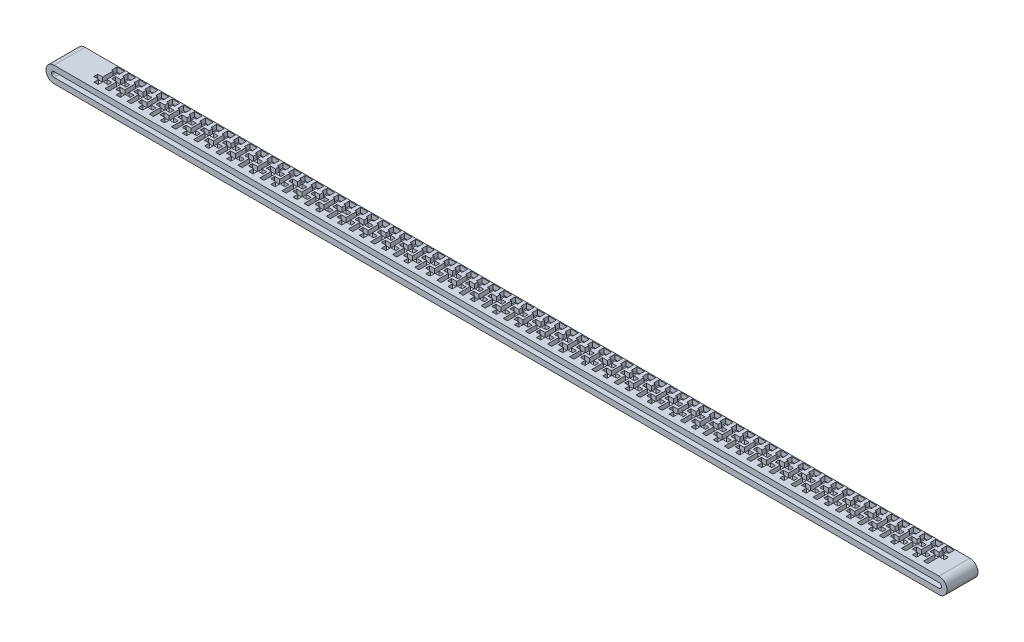
SolidWorks part; units mm, degrees
ref_plane "Front Plane" through (0, 0, 0) normal (0, 0, 1) x (1, 0, 0)
ref_plane "Top Plane" through (0, 0, 0) normal (0, 1, 0) x (1, 0, 0)
ref_plane "Right Plane" through (0, 0, 0) normal (1, 0, 0) x (0, 0, -1)
sketch "Sketch1" plane through (0, 0, 0) normal (0, 0, 1) x (1, 0, 0)
  line L0 (-3934.062, 14.5352) -> (65.938, 14.5352)
  line L2 (65.938, -8.2353) -> (-3934.062, -8.2353)
  line L3 (-3934.062, 39.5352) -> (65.938, 39.5352)
  line L4 (65.938, -33.2353) -> (-3934.062, -33.2353)
  arc A0 (65.938, 14.5352) -> (65.938, -8.2353) centre (65.938, 3.1499) cw
  arc A2 (-3934.062, -8.2353) -> (-3934.062, 14.5352) centre (-3934.062, 3.1499) cw
  arc A3 (-3934.062, -33.2353) -> (-3934.062, 39.5352) centre (-3934.062, 3.1499) cw
  arc A4 (65.938, 39.5352) -> (65.938, -33.2353) centre (65.938, 3.1499) cw
  dimension "D2" = 4000
  dimension "D1" = 25
extrude "Boss-Extrude1" add sketch "Sketch1" along normal blind 140
sketch "Sketch2" plane through (0, 39.5352, 0) normal (0, 1, 0) x (1, 0, 0)
  line L0 (-3777.6067, -116.121) -> (-3758.6067, -116.121)
  line L1 (-3758.6067, -116.121) -> (-3758.6067, -93.6164)
  line L2 (-3758.6067, -93.6164) -> (-3736.1067, -93.6164)
  line L3 (-3736.1067, -93.6164) -> (-3736.1067, -76.5)
  line L4 (-3736.1067, -76.5) -> (-3758.6067, -76.5)
  line L5 (-3758.6067, -76.5) -> (-3758.6067, -29.121)
  line L6 (-3758.6067, -29.121) -> (-3751.1067, -29.121)
  line L7 (-3751.1067, -29.121) -> (-3751.1067, -4.121)
  line L8 (-3751.1067, -4.121) -> (-3785.1067, -4.121)
  line L9 (-3785.1067, -4.121) -> (-3785.1067, -29.121)
  line L10 (-3785.1067, -29.121) -> (-3777.6067, -29.121)
  line L11 (-3777.6067, -29.121) -> (-3777.6067, -76.5)
  line L12 (-3777.6067, -76.5) -> (-3800.1067, -76.5)
  line L13 (-3800.1067, -76.5) -> (-3800.1067, -94.5)
  line L14 (-3800.1067, -94.5) -> (-3777.6067, -94.5)
  line L15 (-3777.6067, -94.5) -> (-3777.6067, -116.121)
  line L16 (65.938, -140) -> (-3934.062, -140) construction
  line L17 (-3727.6067, -116.121) -> (-3708.6067, -116.121)
  line L18 (-3708.6067, -116.121) -> (-3708.6067, -63.5)
  line L19 (-3708.6067, -63.5) -> (-3686.1067, -63.5)
  line L20 (-3686.1067, -63.5) -> (-3686.1067, -45.5)
  line L21 (-3686.1067, -45.5) -> (-3708.6067, -45.5)
  line L22 (-3708.6067, -45.5) -> (-3708.6067, -29.121)
  line L23 (-3708.6067, -29.121) -> (-3701.1067, -29.121)
  line L24 (-3701.1067, -29.121) -> (-3701.1067, -4.121)
  line L25 (-3701.1067, -4.121) -> (-3735.1067, -4.121)
  line L26 (-3735.1067, -4.121) -> (-3735.1067, -29.121)
  line L27 (-3735.1067, -29.121) -> (-3727.6067, -29.121)
  line L28 (-3727.6067, -29.121) -> (-3727.6067, -45.5)
  line L29 (-3727.6067, -45.5) -> (-3750.1067, -45.5)
  line L30 (-3750.1067, -45.5) -> (-3750.1067, -63.5)
  line L31 (-3750.1067, -63.5) -> (-3727.6067, -63.5)
  line L32 (-3727.6067, -63.5) -> (-3727.6067, -116.121)
  line L33 (65.938, 0) -> (-3934.062, 0) construction
  line L34 (-3768.1067, 46.1112) -> (-3768.1067, -145.1628) construction
  line L35 (-3718.1067, 41.1055) -> (-3718.1067, -145.1628) construction
  line L36 (-3677.6067, -94.5) -> (-3677.6067, -116.121)
  line L37 (-3677.6067, -116.121) -> (-3658.6067, -116.121)
  line L38 (-3658.6067, -116.121) -> (-3658.6067, -93.6164)
  line L39 (-3658.6067, -93.6164) -> (-3636.1067, -93.6164)
  line L40 (-3636.1067, -93.6164) -> (-3636.1067, -76.5)
  line L41 (-3636.1067, -76.5) -> (-3658.6067, -76.5)
  line L42 (-3658.6067, -76.5) -> (-3658.6067, -29.121)
  line L43 (-3658.6067, -29.121) -> (-3651.1067, -29.121)
  line L44 (-3651.1067, -29.121) -> (-3651.1067, -4.121)
  line L45 (-3651.1067, -4.121) -> (-3685.1067, -4.121)
  line L46 (-3685.1067, -4.121) -> (-3685.1067, -29.121)
  line L47 (-3685.1067, -29.121) -> (-3677.6067, -29.121)
  line L48 (-3677.6067, -29.121) -> (-3677.6067, -76.5)
  line L49 (-3677.6067, -76.5) -> (-3700.1067, -76.5)
  line L50 (-3700.1067, -76.5) -> (-3700.1067, -94.5)
  line L51 (-3700.1067, -94.5) -> (-3677.6067, -94.5)
  line L52 (-3577.6067, -94.5) -> (-3577.6067, -116.121)
  line L53 (-3577.6067, -116.121) -> (-3558.6067, -116.121)
  line L54 (-3558.6067, -116.121) -> (-3558.6067, -93.6164)
  line L55 (-3558.6067, -93.6164) -> (-3536.1067, -93.6164)
  line L56 (-3536.1067, -93.6164) -> (-3536.1067, -76.5)
  line L57 (-3536.1067, -76.5) -> (-3558.6067, -76.5)
  line L58 (-3558.6067, -76.5) -> (-3558.6067, -29.121)
  line L59 (-3558.6067, -29.121) -> (-3551.1067, -29.121)
  line L60 (-3551.1067, -29.121) -> (-3551.1067, -4.121)
  line L61 (-3551.1067, -4.121) -> (-3585.1067, -4.121)
  line L62 (-3585.1067, -4.121) -> (-3585.1067, -29.121)
  line L63 (-3585.1067, -29.121) -> (-3577.6067, -29.121)
  line L64 (-3577.6067, -29.121) -> (-3577.6067, -76.5)
  line L65 (-3577.6067, -76.5) -> (-3600.1067, -76.5)
  line L66 (-3600.1067, -76.5) -> (-3600.1067, -94.5)
  line L67 (-3600.1067, -94.5) -> (-3577.6067, -94.5)
  line L68 (-3477.6067, -94.5) -> (-3477.6067, -116.121)
  line L69 (-3477.6067, -116.121) -> (-3458.6067, -116.121)
  line L70 (-3458.6067, -116.121) -> (-3458.6067, -93.6164)
  line L71 (-3458.6067, -93.6164) -> (-3436.1067, -93.6164)
  line L72 (-3436.1067, -93.6164) -> (-3436.1067, -76.5)
  line L73 (-3436.1067, -76.5) -> (-3458.6067, -76.5)
  line L74 (-3458.6067, -76.5) -> (-3458.6067, -29.121)
  line L75 (-3458.6067, -29.121) -> (-3451.1067, -29.121)
  line L76 (-3451.1067, -29.121) -> (-3451.1067, -4.121)
  line L77 (-3451.1067, -4.121) -> (-3485.1067, -4.121)
  line L78 (-3485.1067, -4.121) -> (-3485.1067, -29.121)
  line L79 (-3485.1067, -29.121) -> (-3477.6067, -29.121)
  line L80 (-3477.6067, -29.121) -> (-3477.6067, -76.5)
  line L81 (-3477.6067, -76.5) -> (-3500.1067, -76.5)
  line L82 (-3500.1067, -76.5) -> (-3500.1067, -94.5)
  line L83 (-3500.1067, -94.5) -> (-3477.6067, -94.5)
  line L84 (-3377.6067, -94.5) -> (-3377.6067, -116.121)
  line L85 (-3377.6067, -116.121) -> (-3358.6067, -116.121)
  line L86 (-3358.6067, -116.121) -> (-3358.6067, -93.6164)
  line L87 (-3358.6067, -93.6164) -> (-3336.1067, -93.6164)
  line L88 (-3336.1067, -93.6164) -> (-3336.1067, -76.5)
  line L89 (-3336.1067, -76.5) -> (-3358.6067, -76.5)
  line L90 (-3358.6067, -76.5) -> (-3358.6067, -29.121)
  line L91 (-3358.6067, -29.121) -> (-3351.1067, -29.121)
  line L92 (-3351.1067, -29.121) -> (-3351.1067, -4.121)
  line L93 (-3351.1067, -4.121) -> (-3385.1067, -4.121)
  line L94 (-3385.1067, -4.121) -> (-3385.1067, -29.121)
  line L95 (-3385.1067, -29.121) -> (-3377.6067, -29.121)
  line L96 (-3377.6067, -29.121) -> (-3377.6067, -76.5)
  line L97 (-3377.6067, -76.5) -> (-3400.1067, -76.5)
  line L98 (-3400.1067, -76.5) -> (-3400.1067, -94.5)
  line L99 (-3400.1067, -94.5) -> (-3377.6067, -94.5)
  line L100 (-3277.6067, -94.5) -> (-3277.6067, -116.121)
  line L101 (-3277.6067, -116.121) -> (-3258.6067, -116.121)
  line L102 (-3258.6067, -116.121) -> (-3258.6067, -93.6164)
  line L103 (-3258.6067, -93.6164) -> (-3236.1067, -93.6164)
  line L104 (-3236.1067, -93.6164) -> (-3236.1067, -76.5)
  line L105 (-3236.1067, -76.5) -> (-3258.6067, -76.5)
  line L106 (-3258.6067, -76.5) -> (-3258.6067, -29.121)
  line L107 (-3258.6067, -29.121) -> (-3251.1067, -29.121)
  line L108 (-3251.1067, -29.121) -> (-3251.1067, -4.121)
  line L109 (-3251.1067, -4.121) -> (-3285.1067, -4.121)
  line L110 (-3285.1067, -4.121) -> (-3285.1067, -29.121)
  line L111 (-3285.1067, -29.121) -> (-3277.6067, -29.121)
  line L112 (-3277.6067, -29.121) -> (-3277.6067, -76.5)
  line L113 (-3277.6067, -76.5) -> (-3300.1067, -76.5)
  line L114 (-3300.1067, -76.5) -> (-3300.1067, -94.5)
  line L115 (-3300.1067, -94.5) -> (-3277.6067, -94.5)
  line L116 (-3177.6067, -94.5) -> (-3177.6067, -116.121)
  line L117 (-3177.6067, -116.121) -> (-3158.6067, -116.121)
  line L118 (-3158.6067, -116.121) -> (-3158.6067, -93.6164)
  line L119 (-3158.6067, -93.6164) -> (-3136.1067, -93.6164)
  line L120 (-3136.1067, -93.6164) -> (-3136.1067, -76.5)
  line L121 (-3136.1067, -76.5) -> (-3158.6067, -76.5)
  line L122 (-3158.6067, -76.5) -> (-3158.6067, -29.121)
  line L123 (-3158.6067, -29.121) -> (-3151.1067, -29.121)
  line L124 (-3151.1067, -29.121) -> (-3151.1067, -4.121)
  line L125 (-3151.1067, -4.121) -> (-3185.1067, -4.121)
  line L126 (-3185.1067, -4.121) -> (-3185.1067, -29.121)
  line L127 (-3185.1067, -29.121) -> (-3177.6067, -29.121)
  line L128 (-3177.6067, -29.121) -> (-3177.6067, -76.5)
  line L129 (-3177.6067, -76.5) -> (-3200.1067, -76.5)
  line L130 (-3200.1067, -76.5) -> (-3200.1067, -94.5)
  line L131 (-3200.1067, -94.5) -> (-3177.6067, -94.5)
  line L132 (-3077.6067, -94.5) -> (-3077.6067, -116.121)
  line L133 (-3077.6067, -116.121) -> (-3058.6067, -116.121)
  line L134 (-3058.6067, -116.121) -> (-3058.6067, -93.6164)
  line L135 (-3058.6067, -93.6164) -> (-3036.1067, -93.6164)
  line L136 (-3036.1067, -93.6164) -> (-3036.1067, -76.5)
  line L137 (-3036.1067, -76.5) -> (-3058.6067, -76.5)
  line L138 (-3058.6067, -76.5) -> (-3058.6067, -29.121)
  line L139 (-3058.6067, -29.121) -> (-3051.1067, -29.121)
  line L140 (-3051.1067, -29.121) -> (-3051.1067, -4.121)
  line L141 (-3051.1067, -4.121) -> (-3085.1067, -4.121)
  line L142 (-3085.1067, -4.121) -> (-3085.1067, -29.121)
  line L143 (-3085.1067, -29.121) -> (-3077.6067, -29.121)
  line L144 (-3077.6067, -29.121) -> (-3077.6067, -76.5)
  line L145 (-3077.6067, -76.5) -> (-3100.1067, -76.5)
  line L146 (-3100.1067, -76.5) -> (-3100.1067, -94.5)
  line L147 (-3100.1067, -94.5) -> (-3077.6067, -94.5)
  line L148 (-2977.6067, -94.5) -> (-2977.6067, -116.121)
  line L149 (-2977.6067, -116.121) -> (-2958.6067, -116.121)
  line L150 (-2958.6067, -116.121) -> (-2958.6067, -93.6164)
  line L151 (-2958.6067, -93.6164) -> (-2936.1067, -93.6164)
  line L152 (-2936.1067, -93.6164) -> (-2936.1067, -76.5)
  line L153 (-2936.1067, -76.5) -> (-2958.6067, -76.5)
  line L154 (-2958.6067, -76.5) -> (-2958.6067, -29.121)
  line L155 (-2958.6067, -29.121) -> (-2951.1067, -29.121)
  line L156 (-2951.1067, -29.121) -> (-2951.1067, -4.121)
  line L157 (-2951.1067, -4.121) -> (-2985.1067, -4.121)
  line L158 (-2985.1067, -4.121) -> (-2985.1067, -29.121)
  line L159 (-2985.1067, -29.121) -> (-2977.6067, -29.121)
  line L160 (-2977.6067, -29.121) -> (-2977.6067, -76.5)
  line L161 (-2977.6067, -76.5) -> (-3000.1067, -76.5)
  line L162 (-3000.1067, -76.5) -> (-3000.1067, -94.5)
  line L163 (-3000.1067, -94.5) -> (-2977.6067, -94.5)
  line L164 (-2877.6067, -94.5) -> (-2877.6067, -116.121)
  line L165 (-2877.6067, -116.121) -> (-2858.6067, -116.121)
  line L166 (-2858.6067, -116.121) -> (-2858.6067, -93.6164)
  line L167 (-2858.6067, -93.6164) -> (-2836.1067, -93.6164)
  line L168 (-2836.1067, -93.6164) -> (-2836.1067, -76.5)
  line L169 (-2836.1067, -76.5) -> (-2858.6067, -76.5)
  line L170 (-2858.6067, -76.5) -> (-2858.6067, -29.121)
  line L171 (-2858.6067, -29.121) -> (-2851.1067, -29.121)
  line L172 (-2851.1067, -29.121) -> (-2851.1067, -4.121)
  line L173 (-2851.1067, -4.121) -> (-2885.1067, -4.121)
  line L174 (-2885.1067, -4.121) -> (-2885.1067, -29.121)
  line L175 (-2885.1067, -29.121) -> (-2877.6067, -29.121)
  line L176 (-2877.6067, -29.121) -> (-2877.6067, -76.5)
  line L177 (-2877.6067, -76.5) -> (-2900.1067, -76.5)
  line L178 (-2900.1067, -76.5) -> (-2900.1067, -94.5)
  line L179 (-2900.1067, -94.5) -> (-2877.6067, -94.5)
  line L180 (-2777.6067, -94.5) -> (-2777.6067, -116.121)
  line L181 (-2777.6067, -116.121) -> (-2758.6067, -116.121)
  line L182 (-2758.6067, -116.121) -> (-2758.6067, -93.6164)
  line L183 (-2758.6067, -93.6164) -> (-2736.1067, -93.6164)
  line L184 (-2736.1067, -93.6164) -> (-2736.1067, -76.5)
  line L185 (-2736.1067, -76.5) -> (-2758.6067, -76.5)
  line L186 (-2758.6067, -76.5) -> (-2758.6067, -29.121)
  line L187 (-2758.6067, -29.121) -> (-2751.1067, -29.121)
  line L188 (-2751.1067, -29.121) -> (-2751.1067, -4.121)
  line L189 (-2751.1067, -4.121) -> (-2785.1067, -4.121)
  line L190 (-2785.1067, -4.121) -> (-2785.1067, -29.121)
  line L191 (-2785.1067, -29.121) -> (-2777.6067, -29.121)
  line L192 (-2777.6067, -29.121) -> (-2777.6067, -76.5)
  line L193 (-2777.6067, -76.5) -> (-2800.1067, -76.5)
  line L194 (-2800.1067, -76.5) -> (-2800.1067, -94.5)
  line L195 (-2800.1067, -94.5) -> (-2777.6067, -94.5)
  line L196 (-2677.6067, -94.5) -> (-2677.6067, -116.121)
  line L197 (-2677.6067, -116.121) -> (-2658.6067, -116.121)
  line L198 (-2658.6067, -116.121) -> (-2658.6067, -93.6164)
  line L199 (-2658.6067, -93.6164) -> (-2636.1067, -93.6164)
  line L200 (-2636.1067, -93.6164) -> (-2636.1067, -76.5)
  line L201 (-2636.1067, -76.5) -> (-2658.6067, -76.5)
  line L202 (-2658.6067, -76.5) -> (-2658.6067, -29.121)
  line L203 (-2658.6067, -29.121) -> (-2651.1067, -29.121)
  line L204 (-2651.1067, -29.121) -> (-2651.1067, -4.121)
  line L205 (-2651.1067, -4.121) -> (-2685.1067, -4.121)
  line L206 (-2685.1067, -4.121) -> (-2685.1067, -29.121)
  line L207 (-2685.1067, -29.121) -> (-2677.6067, -29.121)
  line L208 (-2677.6067, -29.121) -> (-2677.6067, -76.5)
  line L209 (-2677.6067, -76.5) -> (-2700.1067, -76.5)
  line L210 (-2700.1067, -76.5) -> (-2700.1067, -94.5)
  line L211 (-2700.1067, -94.5) -> (-2677.6067, -94.5)
  line L212 (-2577.6067, -94.5) -> (-2577.6067, -116.121)
  line L213 (-2577.6067, -116.121) -> (-2558.6067, -116.121)
  line L214 (-2558.6067, -116.121) -> (-2558.6067, -93.6164)
  line L215 (-2558.6067, -93.6164) -> (-2536.1067, -93.6164)
  line L216 (-2536.1067, -93.6164) -> (-2536.1067, -76.5)
  line L217 (-2536.1067, -76.5) -> (-2558.6067, -76.5)
  line L218 (-2558.6067, -76.5) -> (-2558.6067, -29.121)
  line L219 (-2558.6067, -29.121) -> (-2551.1067, -29.121)
  line L220 (-2551.1067, -29.121) -> (-2551.1067, -4.121)
  line L221 (-2551.1067, -4.121) -> (-2585.1067, -4.121)
  line L222 (-2585.1067, -4.121) -> (-2585.1067, -29.121)
  line L223 (-2585.1067, -29.121) -> (-2577.6067, -29.121)
  line L224 (-2577.6067, -29.121) -> (-2577.6067, -76.5)
  line L225 (-2577.6067, -76.5) -> (-2600.1067, -76.5)
  line L226 (-2600.1067, -76.5) -> (-2600.1067, -94.5)
  line L227 (-2600.1067, -94.5) -> (-2577.6067, -94.5)
  line L228 (-2477.6067, -94.5) -> (-2477.6067, -116.121)
  line L229 (-2477.6067, -116.121) -> (-2458.6067, -116.121)
  line L230 (-2458.6067, -116.121) -> (-2458.6067, -93.6164)
  line L231 (-2458.6067, -93.6164) -> (-2436.1067, -93.6164)
  line L232 (-2436.1067, -93.6164) -> (-2436.1067, -76.5)
  line L233 (-2436.1067, -76.5) -> (-2458.6067, -76.5)
  line L234 (-2458.6067, -76.5) -> (-2458.6067, -29.121)
  line L235 (-2458.6067, -29.121) -> (-2451.1067, -29.121)
  line L236 (-2451.1067, -29.121) -> (-2451.1067, -4.121)
  line L237 (-2451.1067, -4.121) -> (-2485.1067, -4.121)
  line L238 (-2485.1067, -4.121) -> (-2485.1067, -29.121)
  line L239 (-2485.1067, -29.121) -> (-2477.6067, -29.121)
  line L240 (-2477.6067, -29.121) -> (-2477.6067, -76.5)
  line L241 (-2477.6067, -76.5) -> (-2500.1067, -76.5)
  line L242 (-2500.1067, -76.5) -> (-2500.1067, -94.5)
  line L243 (-2500.1067, -94.5) -> (-2477.6067, -94.5)
  line L244 (-2377.6067, -94.5) -> (-2377.6067, -116.121)
  line L245 (-2377.6067, -116.121) -> (-2358.6067, -116.121)
  line L246 (-2358.6067, -116.121) -> (-2358.6067, -93.6164)
  line L247 (-2358.6067, -93.6164) -> (-2336.1067, -93.6164)
  line L248 (-2336.1067, -93.6164) -> (-2336.1067, -76.5)
  line L249 (-2336.1067, -76.5) -> (-2358.6067, -76.5)
  line L250 (-2358.6067, -76.5) -> (-2358.6067, -29.121)
  line L251 (-2358.6067, -29.121) -> (-2351.1067, -29.121)
  line L252 (-2351.1067, -29.121) -> (-2351.1067, -4.121)
  line L253 (-2351.1067, -4.121) -> (-2385.1067, -4.121)
  line L254 (-2385.1067, -4.121) -> (-2385.1067, -29.121)
  line L255 (-2385.1067, -29.121) -> (-2377.6067, -29.121)
  line L256 (-2377.6067, -29.121) -> (-2377.6067, -76.5)
  line L257 (-2377.6067, -76.5) -> (-2400.1067, -76.5)
  line L258 (-2400.1067, -76.5) -> (-2400.1067, -94.5)
  line L259 (-2400.1067, -94.5) -> (-2377.6067, -94.5)
  line L260 (-2277.6067, -94.5) -> (-2277.6067, -116.121)
  line L261 (-2277.6067, -116.121) -> (-2258.6067, -116.121)
  line L262 (-2258.6067, -116.121) -> (-2258.6067, -93.6164)
  line L263 (-2258.6067, -93.6164) -> (-2236.1067, -93.6164)
  line L264 (-2236.1067, -93.6164) -> (-2236.1067, -76.5)
  line L265 (-2236.1067, -76.5) -> (-2258.6067, -76.5)
  line L266 (-2258.6067, -76.5) -> (-2258.6067, -29.121)
  line L267 (-2258.6067, -29.121) -> (-2251.1067, -29.121)
  line L268 (-2251.1067, -29.121) -> (-2251.1067, -4.121)
  line L269 (-2251.1067, -4.121) -> (-2285.1067, -4.121)
  line L270 (-2285.1067, -4.121) -> (-2285.1067, -29.121)
  line L271 (-2285.1067, -29.121) -> (-2277.6067, -29.121)
  line L272 (-2277.6067, -29.121) -> (-2277.6067, -76.5)
  line L273 (-2277.6067, -76.5) -> (-2300.1067, -76.5)
  line L274 (-2300.1067, -76.5) -> (-2300.1067, -94.5)
  line L275 (-2300.1067, -94.5) -> (-2277.6067, -94.5)
  line L276 (-2177.6067, -94.5) -> (-2177.6067, -116.121)
  line L277 (-2177.6067, -116.121) -> (-2158.6067, -116.121)
  line L278 (-2158.6067, -116.121) -> (-2158.6067, -93.6164)
  line L279 (-2158.6067, -93.6164) -> (-2136.1067, -93.6164)
  line L280 (-2136.1067, -93.6164) -> (-2136.1067, -76.5)
  line L281 (-2136.1067, -76.5) -> (-2158.6067, -76.5)
  line L282 (-2158.6067, -76.5) -> (-2158.6067, -29.121)
  line L283 (-2158.6067, -29.121) -> (-2151.1067, -29.121)
  line L284 (-2151.1067, -29.121) -> (-2151.1067, -4.121)
  line L285 (-2151.1067, -4.121) -> (-2185.1067, -4.121)
  line L286 (-2185.1067, -4.121) -> (-2185.1067, -29.121)
  line L287 (-2185.1067, -29.121) -> (-2177.6067, -29.121)
  line L288 (-2177.6067, -29.121) -> (-2177.6067, -76.5)
  line L289 (-2177.6067, -76.5) -> (-2200.1067, -76.5)
  line L290 (-2200.1067, -76.5) -> (-2200.1067, -94.5)
  line L291 (-2200.1067, -94.5) -> (-2177.6067, -94.5)
  line L292 (-2077.6067, -94.5) -> (-2077.6067, -116.121)
  line L293 (-2077.6067, -116.121) -> (-2058.6067, -116.121)
  line L294 (-2058.6067, -116.121) -> (-2058.6067, -93.6164)
  line L295 (-2058.6067, -93.6164) -> (-2036.1067, -93.6164)
  line L296 (-2036.1067, -93.6164) -> (-2036.1067, -76.5)
  line L297 (-2036.1067, -76.5) -> (-2058.6067, -76.5)
  line L298 (-2058.6067, -76.5) -> (-2058.6067, -29.121)
  line L299 (-2058.6067, -29.121) -> (-2051.1067, -29.121)
  line L300 (-2051.1067, -29.121) -> (-2051.1067, -4.121)
  line L301 (-2051.1067, -4.121) -> (-2085.1067, -4.121)
  line L302 (-2085.1067, -4.121) -> (-2085.1067, -29.121)
  line L303 (-2085.1067, -29.121) -> (-2077.6067, -29.121)
  line L304 (-2077.6067, -29.121) -> (-2077.6067, -76.5)
  line L305 (-2077.6067, -76.5) -> (-2100.1067, -76.5)
  line L306 (-2100.1067, -76.5) -> (-2100.1067, -94.5)
  line L307 (-2100.1067, -94.5) -> (-2077.6067, -94.5)
  line L308 (-1977.6067, -94.5) -> (-1977.6067, -116.121)
  line L309 (-1977.6067, -116.121) -> (-1958.6067, -116.121)
  line L310 (-1958.6067, -116.121) -> (-1958.6067, -93.6164)
  line L311 (-1958.6067, -93.6164) -> (-1936.1067, -93.6164)
  line L312 (-1936.1067, -93.6164) -> (-1936.1067, -76.5)
  line L313 (-1936.1067, -76.5) -> (-1958.6067, -76.5)
  line L314 (-1958.6067, -76.5) -> (-1958.6067, -29.121)
  line L315 (-1958.6067, -29.121) -> (-1951.1067, -29.121)
  line L316 (-1951.1067, -29.121) -> (-1951.1067, -4.121)
  line L317 (-1951.1067, -4.121) -> (-1985.1067, -4.121)
  line L318 (-1985.1067, -4.121) -> (-1985.1067, -29.121)
  line L319 (-1985.1067, -29.121) -> (-1977.6067, -29.121)
  line L320 (-1977.6067, -29.121) -> (-1977.6067, -76.5)
  line L321 (-1977.6067, -76.5) -> (-2000.1067, -76.5)
  line L322 (-2000.1067, -76.5) -> (-2000.1067, -94.5)
  line L323 (-2000.1067, -94.5) -> (-1977.6067, -94.5)
  line L324 (-1877.6067, -94.5) -> (-1877.6067, -116.121)
  line L325 (-1877.6067, -116.121) -> (-1858.6067, -116.121)
  line L326 (-1858.6067, -116.121) -> (-1858.6067, -93.6164)
  line L327 (-1858.6067, -93.6164) -> (-1836.1067, -93.6164)
  line L328 (-1836.1067, -93.6164) -> (-1836.1067, -76.5)
  line L329 (-1836.1067, -76.5) -> (-1858.6067, -76.5)
  line L330 (-1858.6067, -76.5) -> (-1858.6067, -29.121)
  line L331 (-1858.6067, -29.121) -> (-1851.1067, -29.121)
  line L332 (-1851.1067, -29.121) -> (-1851.1067, -4.121)
  line L333 (-1851.1067, -4.121) -> (-1885.1067, -4.121)
  line L334 (-1885.1067, -4.121) -> (-1885.1067, -29.121)
  line L335 (-1885.1067, -29.121) -> (-1877.6067, -29.121)
  line L336 (-1877.6067, -29.121) -> (-1877.6067, -76.5)
  line L337 (-1877.6067, -76.5) -> (-1900.1067, -76.5)
  line L338 (-1900.1067, -76.5) -> (-1900.1067, -94.5)
  line L339 (-1900.1067, -94.5) -> (-1877.6067, -94.5)
  line L340 (-1777.6067, -94.5) -> (-1777.6067, -116.121)
  line L341 (-1777.6067, -116.121) -> (-1758.6067, -116.121)
  line L342 (-1758.6067, -116.121) -> (-1758.6067, -93.6164)
  line L343 (-1758.6067, -93.6164) -> (-1736.1067, -93.6164)
  line L344 (-1736.1067, -93.6164) -> (-1736.1067, -76.5)
  line L345 (-1736.1067, -76.5) -> (-1758.6067, -76.5)
  line L346 (-1758.6067, -76.5) -> (-1758.6067, -29.121)
  line L347 (-1758.6067, -29.121) -> (-1751.1067, -29.121)
  line L348 (-1751.1067, -29.121) -> (-1751.1067, -4.121)
  line L349 (-1751.1067, -4.121) -> (-1785.1067, -4.121)
  line L350 (-1785.1067, -4.121) -> (-1785.1067, -29.121)
  line L351 (-1785.1067, -29.121) -> (-1777.6067, -29.121)
  line L352 (-1777.6067, -29.121) -> (-1777.6067, -76.5)
  line L353 (-1777.6067, -76.5) -> (-1800.1067, -76.5)
  line L354 (-1800.1067, -76.5) -> (-1800.1067, -94.5)
  line L355 (-1800.1067, -94.5) -> (-1777.6067, -94.5)
  line L356 (-1677.6067, -94.5) -> (-1677.6067, -116.121)
  line L357 (-1677.6067, -116.121) -> (-1658.6067, -116.121)
  line L358 (-1658.6067, -116.121) -> (-1658.6067, -93.6164)
  line L359 (-1658.6067, -93.6164) -> (-1636.1067, -93.6164)
  line L360 (-1636.1067, -93.6164) -> (-1636.1067, -76.5)
  line L361 (-1636.1067, -76.5) -> (-1658.6067, -76.5)
  line L362 (-1658.6067, -76.5) -> (-1658.6067, -29.121)
  line L363 (-1658.6067, -29.121) -> (-1651.1067, -29.121)
  line L364 (-1651.1067, -29.121) -> (-1651.1067, -4.121)
  line L365 (-1651.1067, -4.121) -> (-1685.1067, -4.121)
  line L366 (-1685.1067, -4.121) -> (-1685.1067, -29.121)
  line L367 (-1685.1067, -29.121) -> (-1677.6067, -29.121)
  line L368 (-1677.6067, -29.121) -> (-1677.6067, -76.5)
  line L369 (-1677.6067, -76.5) -> (-1700.1067, -76.5)
  line L370 (-1700.1067, -76.5) -> (-1700.1067, -94.5)
  line L371 (-1700.1067, -94.5) -> (-1677.6067, -94.5)
  line L372 (-1577.6067, -94.5) -> (-1577.6067, -116.121)
  line L373 (-1577.6067, -116.121) -> (-1558.6067, -116.121)
  line L374 (-1558.6067, -116.121) -> (-1558.6067, -93.6164)
  line L375 (-1558.6067, -93.6164) -> (-1536.1067, -93.6164)
  line L376 (-1536.1067, -93.6164) -> (-1536.1067, -76.5)
  line L377 (-1536.1067, -76.5) -> (-1558.6067, -76.5)
  line L378 (-1558.6067, -76.5) -> (-1558.6067, -29.121)
  line L379 (-1558.6067, -29.121) -> (-1551.1067, -29.121)
  line L380 (-1551.1067, -29.121) -> (-1551.1067, -4.121)
  line L381 (-1551.1067, -4.121) -> (-1585.1067, -4.121)
  line L382 (-1585.1067, -4.121) -> (-1585.1067, -29.121)
  line L383 (-1585.1067, -29.121) -> (-1577.6067, -29.121)
  line L384 (-1577.6067, -29.121) -> (-1577.6067, -76.5)
  line L385 (-1577.6067, -76.5) -> (-1600.1067, -76.5)
  line L386 (-1600.1067, -76.5) -> (-1600.1067, -94.5)
  line L387 (-1600.1067, -94.5) -> (-1577.6067, -94.5)
  line L388 (-1477.6067, -94.5) -> (-1477.6067, -116.121)
  line L389 (-1477.6067, -116.121) -> (-1458.6067, -116.121)
  line L390 (-1458.6067, -116.121) -> (-1458.6067, -93.6164)
  line L391 (-1458.6067, -93.6164) -> (-1436.1067, -93.6164)
  line L392 (-1436.1067, -93.6164) -> (-1436.1067, -76.5)
  line L393 (-1436.1067, -76.5) -> (-1458.6067, -76.5)
  line L394 (-1458.6067, -76.5) -> (-1458.6067, -29.121)
  line L395 (-1458.6067, -29.121) -> (-1451.1067, -29.121)
  line L396 (-1451.1067, -29.121) -> (-1451.1067, -4.121)
  line L397 (-1451.1067, -4.121) -> (-1485.1067, -4.121)
  line L398 (-1485.1067, -4.121) -> (-1485.1067, -29.121)
  line L399 (-1485.1067, -29.121) -> (-1477.6067, -29.121)
  line L400 (-1477.6067, -29.121) -> (-1477.6067, -76.5)
  line L401 (-1477.6067, -76.5) -> (-1500.1067, -76.5)
  line L402 (-1500.1067, -76.5) -> (-1500.1067, -94.5)
  line L403 (-1500.1067, -94.5) -> (-1477.6067, -94.5)
  line L404 (-1377.6067, -94.5) -> (-1377.6067, -116.121)
  line L405 (-1377.6067, -116.121) -> (-1358.6067, -116.121)
  line L406 (-1358.6067, -116.121) -> (-1358.6067, -93.6164)
  line L407 (-1358.6067, -93.6164) -> (-1336.1067, -93.6164)
  line L408 (-1336.1067, -93.6164) -> (-1336.1067, -76.5)
  line L409 (-1336.1067, -76.5) -> (-1358.6067, -76.5)
  line L410 (-1358.6067, -76.5) -> (-1358.6067, -29.121)
  line L411 (-1358.6067, -29.121) -> (-1351.1067, -29.121)
  line L412 (-1351.1067, -29.121) -> (-1351.1067, -4.121)
  line L413 (-1351.1067, -4.121) -> (-1385.1067, -4.121)
  line L414 (-1385.1067, -4.121) -> (-1385.1067, -29.121)
  line L415 (-1385.1067, -29.121) -> (-1377.6067, -29.121)
  line L416 (-1377.6067, -29.121) -> (-1377.6067, -76.5)
  line L417 (-1377.6067, -76.5) -> (-1400.1067, -76.5)
  line L418 (-1400.1067, -76.5) -> (-1400.1067, -94.5)
  line L419 (-1400.1067, -94.5) -> (-1377.6067, -94.5)
  line L420 (-1277.6067, -94.5) -> (-1277.6067, -116.121)
  line L421 (-1277.6067, -116.121) -> (-1258.6067, -116.121)
  line L422 (-1258.6067, -116.121) -> (-1258.6067, -93.6164)
  line L423 (-1258.6067, -93.6164) -> (-1236.1067, -93.6164)
  line L424 (-1236.1067, -93.6164) -> (-1236.1067, -76.5)
  line L425 (-1236.1067, -76.5) -> (-1258.6067, -76.5)
  line L426 (-1258.6067, -76.5) -> (-1258.6067, -29.121)
  line L427 (-1258.6067, -29.121) -> (-1251.1067, -29.121)
  line L428 (-1251.1067, -29.121) -> (-1251.1067, -4.121)
  line L429 (-1251.1067, -4.121) -> (-1285.1067, -4.121)
  line L430 (-1285.1067, -4.121) -> (-1285.1067, -29.121)
  line L431 (-1285.1067, -29.121) -> (-1277.6067, -29.121)
  line L432 (-1277.6067, -29.121) -> (-1277.6067, -76.5)
  line L433 (-1277.6067, -76.5) -> (-1300.1067, -76.5)
  line L434 (-1300.1067, -76.5) -> (-1300.1067, -94.5)
  line L435 (-1300.1067, -94.5) -> (-1277.6067, -94.5)
  line L436 (-1177.6067, -94.5) -> (-1177.6067, -116.121)
  line L437 (-1177.6067, -116.121) -> (-1158.6067, -116.121)
  line L438 (-1158.6067, -116.121) -> (-1158.6067, -93.6164)
  line L439 (-1158.6067, -93.6164) -> (-1136.1067, -93.6164)
  line L440 (-1136.1067, -93.6164) -> (-1136.1067, -76.5)
  line L441 (-1136.1067, -76.5) -> (-1158.6067, -76.5)
  line L442 (-1158.6067, -76.5) -> (-1158.6067, -29.121)
  line L443 (-1158.6067, -29.121) -> (-1151.1067, -29.121)
  line L444 (-1151.1067, -29.121) -> (-1151.1067, -4.121)
  line L445 (-1151.1067, -4.121) -> (-1185.1067, -4.121)
  line L446 (-1185.1067, -4.121) -> (-1185.1067, -29.121)
  line L447 (-1185.1067, -29.121) -> (-1177.6067, -29.121)
  line L448 (-1177.6067, -29.121) -> (-1177.6067, -76.5)
  line L449 (-1177.6067, -76.5) -> (-1200.1067, -76.5)
  line L450 (-1200.1067, -76.5) -> (-1200.1067, -94.5)
  line L451 (-1200.1067, -94.5) -> (-1177.6067, -94.5)
  line L452 (-1077.6067, -94.5) -> (-1077.6067, -116.121)
  line L453 (-1077.6067, -116.121) -> (-1058.6067, -116.121)
  line L454 (-1058.6067, -116.121) -> (-1058.6067, -93.6164)
  line L455 (-1058.6067, -93.6164) -> (-1036.1067, -93.6164)
  line L456 (-1036.1067, -93.6164) -> (-1036.1067, -76.5)
  line L457 (-1036.1067, -76.5) -> (-1058.6067, -76.5)
  line L458 (-1058.6067, -76.5) -> (-1058.6067, -29.121)
  line L459 (-1058.6067, -29.121) -> (-1051.1067, -29.121)
  line L460 (-1051.1067, -29.121) -> (-1051.1067, -4.121)
  line L461 (-1051.1067, -4.121) -> (-1085.1067, -4.121)
  line L462 (-1085.1067, -4.121) -> (-1085.1067, -29.121)
  line L463 (-1085.1067, -29.121) -> (-1077.6067, -29.121)
  line L464 (-1077.6067, -29.121) -> (-1077.6067, -76.5)
  line L465 (-1077.6067, -76.5) -> (-1100.1067, -76.5)
  line L466 (-1100.1067, -76.5) -> (-1100.1067, -94.5)
  line L467 (-1100.1067, -94.5) -> (-1077.6067, -94.5)
  line L468 (-977.6067, -94.5) -> (-977.6067, -116.121)
  line L469 (-977.6067, -116.121) -> (-958.6067, -116.121)
  line L470 (-958.6067, -116.121) -> (-958.6067, -93.6164)
  line L471 (-958.6067, -93.6164) -> (-936.1067, -93.6164)
  line L472 (-936.1067, -93.6164) -> (-936.1067, -76.5)
  line L473 (-936.1067, -76.5) -> (-958.6067, -76.5)
  line L474 (-958.6067, -76.5) -> (-958.6067, -29.121)
  line L475 (-958.6067, -29.121) -> (-951.1067, -29.121)
  line L476 (-951.1067, -29.121) -> (-951.1067, -4.121)
  line L477 (-951.1067, -4.121) -> (-985.1067, -4.121)
  line L478 (-985.1067, -4.121) -> (-985.1067, -29.121)
  line L479 (-985.1067, -29.121) -> (-977.6067, -29.121)
  line L480 (-977.6067, -29.121) -> (-977.6067, -76.5)
  line L481 (-977.6067, -76.5) -> (-1000.1067, -76.5)
  line L482 (-1000.1067, -76.5) -> (-1000.1067, -94.5)
  line L483 (-1000.1067, -94.5) -> (-977.6067, -94.5)
  line L484 (-877.6067, -94.5) -> (-877.6067, -116.121)
  line L485 (-877.6067, -116.121) -> (-858.6067, -116.121)
  line L486 (-858.6067, -116.121) -> (-858.6067, -93.6164)
  line L487 (-858.6067, -93.6164) -> (-836.1067, -93.6164)
  line L488 (-836.1067, -93.6164) -> (-836.1067, -76.5)
  line L489 (-836.1067, -76.5) -> (-858.6067, -76.5)
  line L490 (-858.6067, -76.5) -> (-858.6067, -29.121)
  line L491 (-858.6067, -29.121) -> (-851.1067, -29.121)
  line L492 (-851.1067, -29.121) -> (-851.1067, -4.121)
  line L493 (-851.1067, -4.121) -> (-885.1067, -4.121)
  line L494 (-885.1067, -4.121) -> (-885.1067, -29.121)
  line L495 (-885.1067, -29.121) -> (-877.6067, -29.121)
  line L496 (-877.6067, -29.121) -> (-877.6067, -76.5)
  line L497 (-877.6067, -76.5) -> (-900.1067, -76.5)
  line L498 (-900.1067, -76.5) -> (-900.1067, -94.5)
  line L499 (-900.1067, -94.5) -> (-877.6067, -94.5)
  line L500 (-777.6067, -94.5) -> (-777.6067, -116.121)
  line L501 (-777.6067, -116.121) -> (-758.6067, -116.121)
  line L502 (-758.6067, -116.121) -> (-758.6067, -93.6164)
  line L503 (-758.6067, -93.6164) -> (-736.1067, -93.6164)
  line L504 (-736.1067, -93.6164) -> (-736.1067, -76.5)
  line L505 (-736.1067, -76.5) -> (-758.6067, -76.5)
  line L506 (-758.6067, -76.5) -> (-758.6067, -29.121)
  line L507 (-758.6067, -29.121) -> (-751.1067, -29.121)
  line L508 (-751.1067, -29.121) -> (-751.1067, -4.121)
  line L509 (-751.1067, -4.121) -> (-785.1067, -4.121)
  line L510 (-785.1067, -4.121) -> (-785.1067, -29.121)
  line L511 (-785.1067, -29.121) -> (-777.6067, -29.121)
  line L512 (-777.6067, -29.121) -> (-777.6067, -76.5)
  line L513 (-777.6067, -76.5) -> (-800.1067, -76.5)
  line L514 (-800.1067, -76.5) -> (-800.1067, -94.5)
  line L515 (-800.1067, -94.5) -> (-777.6067, -94.5)
  line L516 (-677.6067, -94.5) -> (-677.6067, -116.121)
  line L517 (-677.6067, -116.121) -> (-658.6067, -116.121)
  line L518 (-658.6067, -116.121) -> (-658.6067, -93.6164)
  line L519 (-658.6067, -93.6164) -> (-636.1067, -93.6164)
  line L520 (-636.1067, -93.6164) -> (-636.1067, -76.5)
  line L521 (-636.1067, -76.5) -> (-658.6067, -76.5)
  line L522 (-658.6067, -76.5) -> (-658.6067, -29.121)
  line L523 (-658.6067, -29.121) -> (-651.1067, -29.121)
  line L524 (-651.1067, -29.121) -> (-651.1067, -4.121)
  line L525 (-651.1067, -4.121) -> (-685.1067, -4.121)
  line L526 (-685.1067, -4.121) -> (-685.1067, -29.121)
  line L527 (-685.1067, -29.121) -> (-677.6067, -29.121)
  line L528 (-677.6067, -29.121) -> (-677.6067, -76.5)
  line L529 (-677.6067, -76.5) -> (-700.1067, -76.5)
  line L530 (-700.1067, -76.5) -> (-700.1067, -94.5)
  line L531 (-700.1067, -94.5) -> (-677.6067, -94.5)
  line L532 (-577.6067, -94.5) -> (-577.6067, -116.121)
  line L533 (-577.6067, -116.121) -> (-558.6067, -116.121)
  line L534 (-558.6067, -116.121) -> (-558.6067, -93.6164)
  line L535 (-558.6067, -93.6164) -> (-536.1067, -93.6164)
  line L536 (-536.1067, -93.6164) -> (-536.1067, -76.5)
  line L537 (-536.1067, -76.5) -> (-558.6067, -76.5)
  line L538 (-558.6067, -76.5) -> (-558.6067, -29.121)
  line L539 (-558.6067, -29.121) -> (-551.1067, -29.121)
  line L540 (-551.1067, -29.121) -> (-551.1067, -4.121)
  line L541 (-551.1067, -4.121) -> (-585.1067, -4.121)
  line L542 (-585.1067, -4.121) -> (-585.1067, -29.121)
  line L543 (-585.1067, -29.121) -> (-577.6067, -29.121)
  line L544 (-577.6067, -29.121) -> (-577.6067, -76.5)
  line L545 (-577.6067, -76.5) -> (-600.1067, -76.5)
  line L546 (-600.1067, -76.5) -> (-600.1067, -94.5)
  line L547 (-600.1067, -94.5) -> (-577.6067, -94.5)
  line L548 (-477.6067, -94.5) -> (-477.6067, -116.121)
  line L549 (-477.6067, -116.121) -> (-458.6067, -116.121)
  line L550 (-458.6067, -116.121) -> (-458.6067, -93.6164)
  line L551 (-458.6067, -93.6164) -> (-436.1067, -93.6164)
  line L552 (-436.1067, -93.6164) -> (-436.1067, -76.5)
  line L553 (-436.1067, -76.5) -> (-458.6067, -76.5)
  line L554 (-458.6067, -76.5) -> (-458.6067, -29.121)
  line L555 (-458.6067, -29.121) -> (-451.1067, -29.121)
  line L556 (-451.1067, -29.121) -> (-451.1067, -4.121)
  line L557 (-451.1067, -4.121) -> (-485.1067, -4.121)
  line L558 (-485.1067, -4.121) -> (-485.1067, -29.121)
  line L559 (-485.1067, -29.121) -> (-477.6067, -29.121)
  line L560 (-477.6067, -29.121) -> (-477.6067, -76.5)
  line L561 (-477.6067, -76.5) -> (-500.1067, -76.5)
  line L562 (-500.1067, -76.5) -> (-500.1067, -94.5)
  line L563 (-500.1067, -94.5) -> (-477.6067, -94.5)
  line L564 (-377.6067, -94.5) -> (-377.6067, -116.121)
  line L565 (-377.6067, -116.121) -> (-358.6067, -116.121)
  line L566 (-358.6067, -116.121) -> (-358.6067, -93.6164)
  line L567 (-358.6067, -93.6164) -> (-336.1067, -93.6164)
  line L568 (-336.1067, -93.6164) -> (-336.1067, -76.5)
  line L569 (-336.1067, -76.5) -> (-358.6067, -76.5)
  line L570 (-358.6067, -76.5) -> (-358.6067, -29.121)
  line L571 (-358.6067, -29.121) -> (-351.1067, -29.121)
  line L572 (-351.1067, -29.121) -> (-351.1067, -4.121)
  line L573 (-351.1067, -4.121) -> (-385.1067, -4.121)
  line L574 (-385.1067, -4.121) -> (-385.1067, -29.121)
  line L575 (-385.1067, -29.121) -> (-377.6067, -29.121)
  line L576 (-377.6067, -29.121) -> (-377.6067, -76.5)
  line L577 (-377.6067, -76.5) -> (-400.1067, -76.5)
  line L578 (-400.1067, -76.5) -> (-400.1067, -94.5)
  line L579 (-400.1067, -94.5) -> (-377.6067, -94.5)
  line L580 (-277.6067, -94.5) -> (-277.6067, -116.121)
  line L581 (-277.6067, -116.121) -> (-258.6067, -116.121)
  line L582 (-258.6067, -116.121) -> (-258.6067, -93.6164)
  line L583 (-258.6067, -93.6164) -> (-236.1067, -93.6164)
  line L584 (-236.1067, -93.6164) -> (-236.1067, -76.5)
  line L585 (-236.1067, -76.5) -> (-258.6067, -76.5)
  line L586 (-258.6067, -76.5) -> (-258.6067, -29.121)
  line L587 (-258.6067, -29.121) -> (-251.1067, -29.121)
  line L588 (-251.1067, -29.121) -> (-251.1067, -4.121)
  line L589 (-251.1067, -4.121) -> (-285.1067, -4.121)
  line L590 (-285.1067, -4.121) -> (-285.1067, -29.121)
  line L591 (-285.1067, -29.121) -> (-277.6067, -29.121)
  line L592 (-277.6067, -29.121) -> (-277.6067, -76.5)
  line L593 (-277.6067, -76.5) -> (-300.1067, -76.5)
  line L594 (-300.1067, -76.5) -> (-300.1067, -94.5)
  line L595 (-300.1067, -94.5) -> (-277.6067, -94.5)
  line L596 (-177.6067, -94.5) -> (-177.6067, -116.121)
  line L597 (-177.6067, -116.121) -> (-158.6067, -116.121)
  line L598 (-158.6067, -116.121) -> (-158.6067, -93.6164)
  line L599 (-158.6067, -93.6164) -> (-136.1067, -93.6164)
  line L600 (-136.1067, -93.6164) -> (-136.1067, -76.5)
  line L601 (-136.1067, -76.5) -> (-158.6067, -76.5)
  line L602 (-158.6067, -76.5) -> (-158.6067, -29.121)
  line L603 (-158.6067, -29.121) -> (-151.1067, -29.121)
  line L604 (-151.1067, -29.121) -> (-151.1067, -4.121)
  line L605 (-151.1067, -4.121) -> (-185.1067, -4.121)
  line L606 (-185.1067, -4.121) -> (-185.1067, -29.121)
  line L607 (-185.1067, -29.121) -> (-177.6067, -29.121)
  line L608 (-177.6067, -29.121) -> (-177.6067, -76.5)
  line L609 (-177.6067, -76.5) -> (-200.1067, -76.5)
  line L610 (-200.1067, -76.5) -> (-200.1067, -94.5)
  line L611 (-200.1067, -94.5) -> (-177.6067, -94.5)
  line L612 (-77.6067, -94.5) -> (-77.6067, -116.121)
  line L613 (-77.6067, -116.121) -> (-58.6067, -116.121)
  line L614 (-58.6067, -116.121) -> (-58.6067, -93.6164)
  line L615 (-58.6067, -93.6164) -> (-36.1067, -93.6164)
  line L616 (-36.1067, -93.6164) -> (-36.1067, -76.5)
  line L617 (-36.1067, -76.5) -> (-58.6067, -76.5)
  line L618 (-58.6067, -76.5) -> (-58.6067, -29.121)
  line L619 (-58.6067, -29.121) -> (-51.1067, -29.121)
  line L620 (-51.1067, -29.121) -> (-51.1067, -4.121)
  line L621 (-51.1067, -4.121) -> (-85.1067, -4.121)
  line L622 (-85.1067, -4.121) -> (-85.1067, -29.121)
  line L623 (-85.1067, -29.121) -> (-77.6067, -29.121)
  line L624 (-77.6067, -29.121) -> (-77.6067, -76.5)
  line L625 (-77.6067, -76.5) -> (-100.1067, -76.5)
  line L626 (-100.1067, -76.5) -> (-100.1067, -94.5)
  line L627 (-100.1067, -94.5) -> (-77.6067, -94.5)
  line L628 (-3627.6067, -63.5) -> (-3627.6067, -116.121)
  line L629 (-3627.6067, -116.121) -> (-3608.6067, -116.121)
  line L630 (-3608.6067, -116.121) -> (-3608.6067, -63.5)
  line L631 (-3608.6067, -63.5) -> (-3586.1067, -63.5)
  line L632 (-3586.1067, -63.5) -> (-3586.1067, -45.5)
  line L633 (-3586.1067, -45.5) -> (-3608.6067, -45.5)
  line L634 (-3608.6067, -45.5) -> (-3608.6067, -29.121)
  line L635 (-3608.6067, -29.121) -> (-3601.1067, -29.121)
  line L636 (-3601.1067, -29.121) -> (-3601.1067, -4.121)
  line L637 (-3601.1067, -4.121) -> (-3635.1067, -4.121)
  line L638 (-3635.1067, -4.121) -> (-3635.1067, -29.121)
  line L639 (-3635.1067, -29.121) -> (-3627.6067, -29.121)
  line L640 (-3627.6067, -29.121) -> (-3627.6067, -45.5)
  line L641 (-3627.6067, -45.5) -> (-3650.1067, -45.5)
  line L642 (-3650.1067, -45.5) -> (-3650.1067, -63.5)
  line L643 (-3650.1067, -63.5) -> (-3627.6067, -63.5)
  line L644 (-3527.6067, -63.5) -> (-3527.6067, -116.121)
  line L645 (-3527.6067, -116.121) -> (-3508.6067, -116.121)
  line L646 (-3508.6067, -116.121) -> (-3508.6067, -63.5)
  line L647 (-3508.6067, -63.5) -> (-3486.1067, -63.5)
  line L648 (-3486.1067, -63.5) -> (-3486.1067, -45.5)
  line L649 (-3486.1067, -45.5) -> (-3508.6067, -45.5)
  line L650 (-3508.6067, -45.5) -> (-3508.6067, -29.121)
  line L651 (-3508.6067, -29.121) -> (-3501.1067, -29.121)
  line L652 (-3501.1067, -29.121) -> (-3501.1067, -4.121)
  line L653 (-3501.1067, -4.121) -> (-3535.1067, -4.121)
  line L654 (-3535.1067, -4.121) -> (-3535.1067, -29.121)
  line L655 (-3535.1067, -29.121) -> (-3527.6067, -29.121)
  line L656 (-3527.6067, -29.121) -> (-3527.6067, -45.5)
  line L657 (-3527.6067, -45.5) -> (-3550.1067, -45.5)
  line L658 (-3550.1067, -45.5) -> (-3550.1067, -63.5)
  line L659 (-3550.1067, -63.5) -> (-3527.6067, -63.5)
  line L660 (-3427.6067, -63.5) -> (-3427.6067, -116.121)
  line L661 (-3427.6067, -116.121) -> (-3408.6067, -116.121)
  line L662 (-3408.6067, -116.121) -> (-3408.6067, -63.5)
  line L663 (-3408.6067, -63.5) -> (-3386.1067, -63.5)
  line L664 (-3386.1067, -63.5) -> (-3386.1067, -45.5)
  line L665 (-3386.1067, -45.5) -> (-3408.6067, -45.5)
  line L666 (-3408.6067, -45.5) -> (-3408.6067, -29.121)
  line L667 (-3408.6067, -29.121) -> (-3401.1067, -29.121)
  line L668 (-3401.1067, -29.121) -> (-3401.1067, -4.121)
  line L669 (-3401.1067, -4.121) -> (-3435.1067, -4.121)
  line L670 (-3435.1067, -4.121) -> (-3435.1067, -29.121)
  line L671 (-3435.1067, -29.121) -> (-3427.6067, -29.121)
  line L672 (-3427.6067, -29.121) -> (-3427.6067, -45.5)
  line L673 (-3427.6067, -45.5) -> (-3450.1067, -45.5)
  line L674 (-3450.1067, -45.5) -> (-3450.1067, -63.5)
  line L675 (-3450.1067, -63.5) -> (-3427.6067, -63.5)
  line L676 (-3327.6067, -63.5) -> (-3327.6067, -116.121)
  line L677 (-3327.6067, -116.121) -> (-3308.6067, -116.121)
  line L678 (-3308.6067, -116.121) -> (-3308.6067, -63.5)
  line L679 (-3308.6067, -63.5) -> (-3286.1067, -63.5)
  line L680 (-3286.1067, -63.5) -> (-3286.1067, -45.5)
  line L681 (-3286.1067, -45.5) -> (-3308.6067, -45.5)
  line L682 (-3308.6067, -45.5) -> (-3308.6067, -29.121)
  line L683 (-3308.6067, -29.121) -> (-3301.1067, -29.121)
  line L684 (-3301.1067, -29.121) -> (-3301.1067, -4.121)
  line L685 (-3301.1067, -4.121) -> (-3335.1067, -4.121)
  line L686 (-3335.1067, -4.121) -> (-3335.1067, -29.121)
  line L687 (-3335.1067, -29.121) -> (-3327.6067, -29.121)
  line L688 (-3327.6067, -29.121) -> (-3327.6067, -45.5)
  line L689 (-3327.6067, -45.5) -> (-3350.1067, -45.5)
  line L690 (-3350.1067, -45.5) -> (-3350.1067, -63.5)
  line L691 (-3350.1067, -63.5) -> (-3327.6067, -63.5)
  line L692 (-3227.6067, -63.5) -> (-3227.6067, -116.121)
  line L693 (-3227.6067, -116.121) -> (-3208.6067, -116.121)
  line L694 (-3208.6067, -116.121) -> (-3208.6067, -63.5)
  line L695 (-3208.6067, -63.5) -> (-3186.1067, -63.5)
  line L696 (-3186.1067, -63.5) -> (-3186.1067, -45.5)
  line L697 (-3186.1067, -45.5) -> (-3208.6067, -45.5)
  line L698 (-3208.6067, -45.5) -> (-3208.6067, -29.121)
  line L699 (-3208.6067, -29.121) -> (-3201.1067, -29.121)
  line L700 (-3201.1067, -29.121) -> (-3201.1067, -4.121)
  line L701 (-3201.1067, -4.121) -> (-3235.1067, -4.121)
  line L702 (-3235.1067, -4.121) -> (-3235.1067, -29.121)
  line L703 (-3235.1067, -29.121) -> (-3227.6067, -29.121)
  line L704 (-3227.6067, -29.121) -> (-3227.6067, -45.5)
  line L705 (-3227.6067, -45.5) -> (-3250.1067, -45.5)
  line L706 (-3250.1067, -45.5) -> (-3250.1067, -63.5)
  line L707 (-3250.1067, -63.5) -> (-3227.6067, -63.5)
  line L708 (-3127.6067, -63.5) -> (-3127.6067, -116.121)
  line L709 (-3127.6067, -116.121) -> (-3108.6067, -116.121)
  line L710 (-3108.6067, -116.121) -> (-3108.6067, -63.5)
  line L711 (-3108.6067, -63.5) -> (-3086.1067, -63.5)
  line L712 (-3086.1067, -63.5) -> (-3086.1067, -45.5)
  line L713 (-3086.1067, -45.5) -> (-3108.6067, -45.5)
  line L714 (-3108.6067, -45.5) -> (-3108.6067, -29.121)
  line L715 (-3108.6067, -29.121) -> (-3101.1067, -29.121)
  line L716 (-3101.1067, -29.121) -> (-3101.1067, -4.121)
  line L717 (-3101.1067, -4.121) -> (-3135.1067, -4.121)
  line L718 (-3135.1067, -4.121) -> (-3135.1067, -29.121)
  line L719 (-3135.1067, -29.121) -> (-3127.6067, -29.121)
  line L720 (-3127.6067, -29.121) -> (-3127.6067, -45.5)
  line L721 (-3127.6067, -45.5) -> (-3150.1067, -45.5)
  line L722 (-3150.1067, -45.5) -> (-3150.1067, -63.5)
  line L723 (-3150.1067, -63.5) -> (-3127.6067, -63.5)
  line L724 (-3027.6067, -63.5) -> (-3027.6067, -116.121)
  line L725 (-3027.6067, -116.121) -> (-3008.6067, -116.121)
  line L726 (-3008.6067, -116.121) -> (-3008.6067, -63.5)
  line L727 (-3008.6067, -63.5) -> (-2986.1067, -63.5)
  line L728 (-2986.1067, -63.5) -> (-2986.1067, -45.5)
  line L729 (-2986.1067, -45.5) -> (-3008.6067, -45.5)
  line L730 (-3008.6067, -45.5) -> (-3008.6067, -29.121)
  line L731 (-3008.6067, -29.121) -> (-3001.1067, -29.121)
  line L732 (-3001.1067, -29.121) -> (-3001.1067, -4.121)
  line L733 (-3001.1067, -4.121) -> (-3035.1067, -4.121)
  line L734 (-3035.1067, -4.121) -> (-3035.1067, -29.121)
  line L735 (-3035.1067, -29.121) -> (-3027.6067, -29.121)
  line L736 (-3027.6067, -29.121) -> (-3027.6067, -45.5)
  line L737 (-3027.6067, -45.5) -> (-3050.1067, -45.5)
  line L738 (-3050.1067, -45.5) -> (-3050.1067, -63.5)
  line L739 (-3050.1067, -63.5) -> (-3027.6067, -63.5)
  line L740 (-2927.6067, -63.5) -> (-2927.6067, -116.121)
  line L741 (-2927.6067, -116.121) -> (-2908.6067, -116.121)
  line L742 (-2908.6067, -116.121) -> (-2908.6067, -63.5)
  line L743 (-2908.6067, -63.5) -> (-2886.1067, -63.5)
  line L744 (-2886.1067, -63.5) -> (-2886.1067, -45.5)
  line L745 (-2886.1067, -45.5) -> (-2908.6067, -45.5)
  line L746 (-2908.6067, -45.5) -> (-2908.6067, -29.121)
  line L747 (-2908.6067, -29.121) -> (-2901.1067, -29.121)
  line L748 (-2901.1067, -29.121) -> (-2901.1067, -4.121)
  line L749 (-2901.1067, -4.121) -> (-2935.1067, -4.121)
  line L750 (-2935.1067, -4.121) -> (-2935.1067, -29.121)
  line L751 (-2935.1067, -29.121) -> (-2927.6067, -29.121)
  line L752 (-2927.6067, -29.121) -> (-2927.6067, -45.5)
  line L753 (-2927.6067, -45.5) -> (-2950.1067, -45.5)
  line L754 (-2950.1067, -45.5) -> (-2950.1067, -63.5)
  line L755 (-2950.1067, -63.5) -> (-2927.6067, -63.5)
  line L756 (-2827.6067, -63.5) -> (-2827.6067, -116.121)
  line L757 (-2827.6067, -116.121) -> (-2808.6067, -116.121)
  line L758 (-2808.6067, -116.121) -> (-2808.6067, -63.5)
  line L759 (-2808.6067, -63.5) -> (-2786.1067, -63.5)
  line L760 (-2786.1067, -63.5) -> (-2786.1067, -45.5)
  line L761 (-2786.1067, -45.5) -> (-2808.6067, -45.5)
  line L762 (-2808.6067, -45.5) -> (-2808.6067, -29.121)
  line L763 (-2808.6067, -29.121) -> (-2801.1067, -29.121)
  line L764 (-2801.1067, -29.121) -> (-2801.1067, -4.121)
  line L765 (-2801.1067, -4.121) -> (-2835.1067, -4.121)
  line L766 (-2835.1067, -4.121) -> (-2835.1067, -29.121)
  line L767 (-2835.1067, -29.121) -> (-2827.6067, -29.121)
  line L768 (-2827.6067, -29.121) -> (-2827.6067, -45.5)
  line L769 (-2827.6067, -45.5) -> (-2850.1067, -45.5)
  line L770 (-2850.1067, -45.5) -> (-2850.1067, -63.5)
  line L771 (-2850.1067, -63.5) -> (-2827.6067, -63.5)
  line L772 (-2727.6067, -63.5) -> (-2727.6067, -116.121)
  line L773 (-2727.6067, -116.121) -> (-2708.6067, -116.121)
  line L774 (-2708.6067, -116.121) -> (-2708.6067, -63.5)
  line L775 (-2708.6067, -63.5) -> (-2686.1067, -63.5)
  line L776 (-2686.1067, -63.5) -> (-2686.1067, -45.5)
  line L777 (-2686.1067, -45.5) -> (-2708.6067, -45.5)
  line L778 (-2708.6067, -45.5) -> (-2708.6067, -29.121)
  line L779 (-2708.6067, -29.121) -> (-2701.1067, -29.121)
  line L780 (-2701.1067, -29.121) -> (-2701.1067, -4.121)
  line L781 (-2701.1067, -4.121) -> (-2735.1067, -4.121)
  line L782 (-2735.1067, -4.121) -> (-2735.1067, -29.121)
  line L783 (-2735.1067, -29.121) -> (-2727.6067, -29.121)
  line L784 (-2727.6067, -29.121) -> (-2727.6067, -45.5)
  line L785 (-2727.6067, -45.5) -> (-2750.1067, -45.5)
  line L786 (-2750.1067, -45.5) -> (-2750.1067, -63.5)
  line L787 (-2750.1067, -63.5) -> (-2727.6067, -63.5)
  line L788 (-2627.6067, -63.5) -> (-2627.6067, -116.121)
  line L789 (-2627.6067, -116.121) -> (-2608.6067, -116.121)
  line L790 (-2608.6067, -116.121) -> (-2608.6067, -63.5)
  line L791 (-2608.6067, -63.5) -> (-2586.1067, -63.5)
  line L792 (-2586.1067, -63.5) -> (-2586.1067, -45.5)
  line L793 (-2586.1067, -45.5) -> (-2608.6067, -45.5)
  line L794 (-2608.6067, -45.5) -> (-2608.6067, -29.121)
  line L795 (-2608.6067, -29.121) -> (-2601.1067, -29.121)
  line L796 (-2601.1067, -29.121) -> (-2601.1067, -4.121)
  line L797 (-2601.1067, -4.121) -> (-2635.1067, -4.121)
  line L798 (-2635.1067, -4.121) -> (-2635.1067, -29.121)
  line L799 (-2635.1067, -29.121) -> (-2627.6067, -29.121)
  line L800 (-2627.6067, -29.121) -> (-2627.6067, -45.5)
  line L801 (-2627.6067, -45.5) -> (-2650.1067, -45.5)
  line L802 (-2650.1067, -45.5) -> (-2650.1067, -63.5)
  line L803 (-2650.1067, -63.5) -> (-2627.6067, -63.5)
  line L804 (-2527.6067, -63.5) -> (-2527.6067, -116.121)
  line L805 (-2527.6067, -116.121) -> (-2508.6067, -116.121)
  line L806 (-2508.6067, -116.121) -> (-2508.6067, -63.5)
  line L807 (-2508.6067, -63.5) -> (-2486.1067, -63.5)
  line L808 (-2486.1067, -63.5) -> (-2486.1067, -45.5)
  line L809 (-2486.1067, -45.5) -> (-2508.6067, -45.5)
  line L810 (-2508.6067, -45.5) -> (-2508.6067, -29.121)
  line L811 (-2508.6067, -29.121) -> (-2501.1067, -29.121)
  line L812 (-2501.1067, -29.121) -> (-2501.1067, -4.121)
  line L813 (-2501.1067, -4.121) -> (-2535.1067, -4.121)
  line L814 (-2535.1067, -4.121) -> (-2535.1067, -29.121)
  line L815 (-2535.1067, -29.121) -> (-2527.6067, -29.121)
  line L816 (-2527.6067, -29.121) -> (-2527.6067, -45.5)
  line L817 (-2527.6067, -45.5) -> (-2550.1067, -45.5)
  line L818 (-2550.1067, -45.5) -> (-2550.1067, -63.5)
  line L819 (-2550.1067, -63.5) -> (-2527.6067, -63.5)
  line L820 (-2427.6067, -63.5) -> (-2427.6067, -116.121)
  line L821 (-2427.6067, -116.121) -> (-2408.6067, -116.121)
  line L822 (-2408.6067, -116.121) -> (-2408.6067, -63.5)
  line L823 (-2408.6067, -63.5) -> (-2386.1067, -63.5)
  line L824 (-2386.1067, -63.5) -> (-2386.1067, -45.5)
  line L825 (-2386.1067, -45.5) -> (-2408.6067, -45.5)
  line L826 (-2408.6067, -45.5) -> (-2408.6067, -29.121)
  line L827 (-2408.6067, -29.121) -> (-2401.1067, -29.121)
  line L828 (-2401.1067, -29.121) -> (-2401.1067, -4.121)
  line L829 (-2401.1067, -4.121) -> (-2435.1067, -4.121)
  line L830 (-2435.1067, -4.121) -> (-2435.1067, -29.121)
  line L831 (-2435.1067, -29.121) -> (-2427.6067, -29.121)
  line L832 (-2427.6067, -29.121) -> (-2427.6067, -45.5)
  line L833 (-2427.6067, -45.5) -> (-2450.1067, -45.5)
  line L834 (-2450.1067, -45.5) -> (-2450.1067, -63.5)
  line L835 (-2450.1067, -63.5) -> (-2427.6067, -63.5)
  line L836 (-2327.6067, -63.5) -> (-2327.6067, -116.121)
  line L837 (-2327.6067, -116.121) -> (-2308.6067, -116.121)
  line L838 (-2308.6067, -116.121) -> (-2308.6067, -63.5)
  line L839 (-2308.6067, -63.5) -> (-2286.1067, -63.5)
  line L840 (-2286.1067, -63.5) -> (-2286.1067, -45.5)
  line L841 (-2286.1067, -45.5) -> (-2308.6067, -45.5)
  line L842 (-2308.6067, -45.5) -> (-2308.6067, -29.121)
  line L843 (-2308.6067, -29.121) -> (-2301.1067, -29.121)
  line L844 (-2301.1067, -29.121) -> (-2301.1067, -4.121)
  line L845 (-2301.1067, -4.121) -> (-2335.1067, -4.121)
  line L846 (-2335.1067, -4.121) -> (-2335.1067, -29.121)
  line L847 (-2335.1067, -29.121) -> (-2327.6067, -29.121)
  line L848 (-2327.6067, -29.121) -> (-2327.6067, -45.5)
  line L849 (-2327.6067, -45.5) -> (-2350.1067, -45.5)
  line L850 (-2350.1067, -45.5) -> (-2350.1067, -63.5)
  line L851 (-2350.1067, -63.5) -> (-2327.6067, -63.5)
  line L852 (-2227.6067, -63.5) -> (-2227.6067, -116.121)
  line L853 (-2227.6067, -116.121) -> (-2208.6067, -116.121)
  line L854 (-2208.6067, -116.121) -> (-2208.6067, -63.5)
  line L855 (-2208.6067, -63.5) -> (-2186.1067, -63.5)
  line L856 (-2186.1067, -63.5) -> (-2186.1067, -45.5)
  line L857 (-2186.1067, -45.5) -> (-2208.6067, -45.5)
  line L858 (-2208.6067, -45.5) -> (-2208.6067, -29.121)
  line L859 (-2208.6067, -29.121) -> (-2201.1067, -29.121)
  line L860 (-2201.1067, -29.121) -> (-2201.1067, -4.121)
  line L861 (-2201.1067, -4.121) -> (-2235.1067, -4.121)
  line L862 (-2235.1067, -4.121) -> (-2235.1067, -29.121)
  line L863 (-2235.1067, -29.121) -> (-2227.6067, -29.121)
  line L864 (-2227.6067, -29.121) -> (-2227.6067, -45.5)
  line L865 (-2227.6067, -45.5) -> (-2250.1067, -45.5)
  line L866 (-2250.1067, -45.5) -> (-2250.1067, -63.5)
  line L867 (-2250.1067, -63.5) -> (-2227.6067, -63.5)
  line L868 (-2127.6067, -63.5) -> (-2127.6067, -116.121)
  line L869 (-2127.6067, -116.121) -> (-2108.6067, -116.121)
  line L870 (-2108.6067, -116.121) -> (-2108.6067, -63.5)
  line L871 (-2108.6067, -63.5) -> (-2086.1067, -63.5)
  line L872 (-2086.1067, -63.5) -> (-2086.1067, -45.5)
  line L873 (-2086.1067, -45.5) -> (-2108.6067, -45.5)
  line L874 (-2108.6067, -45.5) -> (-2108.6067, -29.121)
  line L875 (-2108.6067, -29.121) -> (-2101.1067, -29.121)
  line L876 (-2101.1067, -29.121) -> (-2101.1067, -4.121)
  line L877 (-2101.1067, -4.121) -> (-2135.1067, -4.121)
  line L878 (-2135.1067, -4.121) -> (-2135.1067, -29.121)
  line L879 (-2135.1067, -29.121) -> (-2127.6067, -29.121)
  line L880 (-2127.6067, -29.121) -> (-2127.6067, -45.5)
  line L881 (-2127.6067, -45.5) -> (-2150.1067, -45.5)
  line L882 (-2150.1067, -45.5) -> (-2150.1067, -63.5)
  line L883 (-2150.1067, -63.5) -> (-2127.6067, -63.5)
  line L884 (-2027.6067, -63.5) -> (-2027.6067, -116.121)
  line L885 (-2027.6067, -116.121) -> (-2008.6067, -116.121)
  line L886 (-2008.6067, -116.121) -> (-2008.6067, -63.5)
  line L887 (-2008.6067, -63.5) -> (-1986.1067, -63.5)
  line L888 (-1986.1067, -63.5) -> (-1986.1067, -45.5)
  line L889 (-1986.1067, -45.5) -> (-2008.6067, -45.5)
  line L890 (-2008.6067, -45.5) -> (-2008.6067, -29.121)
  line L891 (-2008.6067, -29.121) -> (-2001.1067, -29.121)
  line L892 (-2001.1067, -29.121) -> (-2001.1067, -4.121)
  line L893 (-2001.1067, -4.121) -> (-2035.1067, -4.121)
  line L894 (-2035.1067, -4.121) -> (-2035.1067, -29.121)
  line L895 (-2035.1067, -29.121) -> (-2027.6067, -29.121)
  line L896 (-2027.6067, -29.121) -> (-2027.6067, -45.5)
  line L897 (-2027.6067, -45.5) -> (-2050.1067, -45.5)
  line L898 (-2050.1067, -45.5) -> (-2050.1067, -63.5)
  line L899 (-2050.1067, -63.5) -> (-2027.6067, -63.5)
  line L900 (-1927.6067, -63.5) -> (-1927.6067, -116.121)
  line L901 (-1927.6067, -116.121) -> (-1908.6067, -116.121)
  line L902 (-1908.6067, -116.121) -> (-1908.6067, -63.5)
  line L903 (-1908.6067, -63.5) -> (-1886.1067, -63.5)
  line L904 (-1886.1067, -63.5) -> (-1886.1067, -45.5)
  line L905 (-1886.1067, -45.5) -> (-1908.6067, -45.5)
  line L906 (-1908.6067, -45.5) -> (-1908.6067, -29.121)
  line L907 (-1908.6067, -29.121) -> (-1901.1067, -29.121)
  line L908 (-1901.1067, -29.121) -> (-1901.1067, -4.121)
  line L909 (-1901.1067, -4.121) -> (-1935.1067, -4.121)
  line L910 (-1935.1067, -4.121) -> (-1935.1067, -29.121)
  line L911 (-1935.1067, -29.121) -> (-1927.6067, -29.121)
  line L912 (-1927.6067, -29.121) -> (-1927.6067, -45.5)
  line L913 (-1927.6067, -45.5) -> (-1950.1067, -45.5)
  line L914 (-1950.1067, -45.5) -> (-1950.1067, -63.5)
  line L915 (-1950.1067, -63.5) -> (-1927.6067, -63.5)
  line L916 (-1827.6067, -63.5) -> (-1827.6067, -116.121)
  line L917 (-1827.6067, -116.121) -> (-1808.6067, -116.121)
  line L918 (-1808.6067, -116.121) -> (-1808.6067, -63.5)
  line L919 (-1808.6067, -63.5) -> (-1786.1067, -63.5)
  line L920 (-1786.1067, -63.5) -> (-1786.1067, -45.5)
  line L921 (-1786.1067, -45.5) -> (-1808.6067, -45.5)
  line L922 (-1808.6067, -45.5) -> (-1808.6067, -29.121)
  line L923 (-1808.6067, -29.121) -> (-1801.1067, -29.121)
  line L924 (-1801.1067, -29.121) -> (-1801.1067, -4.121)
  line L925 (-1801.1067, -4.121) -> (-1835.1067, -4.121)
  line L926 (-1835.1067, -4.121) -> (-1835.1067, -29.121)
  line L927 (-1835.1067, -29.121) -> (-1827.6067, -29.121)
  line L928 (-1827.6067, -29.121) -> (-1827.6067, -45.5)
  line L929 (-1827.6067, -45.5) -> (-1850.1067, -45.5)
  line L930 (-1850.1067, -45.5) -> (-1850.1067, -63.5)
  line L931 (-1850.1067, -63.5) -> (-1827.6067, -63.5)
  line L932 (-1727.6067, -63.5) -> (-1727.6067, -116.121)
  line L933 (-1727.6067, -116.121) -> (-1708.6067, -116.121)
  line L934 (-1708.6067, -116.121) -> (-1708.6067, -63.5)
  line L935 (-1708.6067, -63.5) -> (-1686.1067, -63.5)
  line L936 (-1686.1067, -63.5) -> (-1686.1067, -45.5)
  line L937 (-1686.1067, -45.5) -> (-1708.6067, -45.5)
  line L938 (-1708.6067, -45.5) -> (-1708.6067, -29.121)
  line L939 (-1708.6067, -29.121) -> (-1701.1067, -29.121)
  line L940 (-1701.1067, -29.121) -> (-1701.1067, -4.121)
  line L941 (-1701.1067, -4.121) -> (-1735.1067, -4.121)
  line L942 (-1735.1067, -4.121) -> (-1735.1067, -29.121)
  line L943 (-1735.1067, -29.121) -> (-1727.6067, -29.121)
  line L944 (-1727.6067, -29.121) -> (-1727.6067, -45.5)
  line L945 (-1727.6067, -45.5) -> (-1750.1067, -45.5)
  line L946 (-1750.1067, -45.5) -> (-1750.1067, -63.5)
  line L947 (-1750.1067, -63.5) -> (-1727.6067, -63.5)
  line L948 (-1627.6067, -63.5) -> (-1627.6067, -116.121)
  line L949 (-1627.6067, -116.121) -> (-1608.6067, -116.121)
  line L950 (-1608.6067, -116.121) -> (-1608.6067, -63.5)
  line L951 (-1608.6067, -63.5) -> (-1586.1067, -63.5)
  line L952 (-1586.1067, -63.5) -> (-1586.1067, -45.5)
  line L953 (-1586.1067, -45.5) -> (-1608.6067, -45.5)
  line L954 (-1608.6067, -45.5) -> (-1608.6067, -29.121)
  line L955 (-1608.6067, -29.121) -> (-1601.1067, -29.121)
  line L956 (-1601.1067, -29.121) -> (-1601.1067, -4.121)
  line L957 (-1601.1067, -4.121) -> (-1635.1067, -4.121)
  line L958 (-1635.1067, -4.121) -> (-1635.1067, -29.121)
  line L959 (-1635.1067, -29.121) -> (-1627.6067, -29.121)
  line L960 (-1627.6067, -29.121) -> (-1627.6067, -45.5)
  line L961 (-1627.6067, -45.5) -> (-1650.1067, -45.5)
  line L962 (-1650.1067, -45.5) -> (-1650.1067, -63.5)
  line L963 (-1650.1067, -63.5) -> (-1627.6067, -63.5)
  line L964 (-1527.6067, -63.5) -> (-1527.6067, -116.121)
  line L965 (-1527.6067, -116.121) -> (-1508.6067, -116.121)
  line L966 (-1508.6067, -116.121) -> (-1508.6067, -63.5)
  line L967 (-1508.6067, -63.5) -> (-1486.1067, -63.5)
  line L968 (-1486.1067, -63.5) -> (-1486.1067, -45.5)
  line L969 (-1486.1067, -45.5) -> (-1508.6067, -45.5)
  line L970 (-1508.6067, -45.5) -> (-1508.6067, -29.121)
  line L971 (-1508.6067, -29.121) -> (-1501.1067, -29.121)
  line L972 (-1501.1067, -29.121) -> (-1501.1067, -4.121)
  line L973 (-1501.1067, -4.121) -> (-1535.1067, -4.121)
  line L974 (-1535.1067, -4.121) -> (-1535.1067, -29.121)
  line L975 (-1535.1067, -29.121) -> (-1527.6067, -29.121)
  line L976 (-1527.6067, -29.121) -> (-1527.6067, -45.5)
  line L977 (-1527.6067, -45.5) -> (-1550.1067, -45.5)
  line L978 (-1550.1067, -45.5) -> (-1550.1067, -63.5)
  line L979 (-1550.1067, -63.5) -> (-1527.6067, -63.5)
  line L980 (-1427.6067, -63.5) -> (-1427.6067, -116.121)
  line L981 (-1427.6067, -116.121) -> (-1408.6067, -116.121)
  line L982 (-1408.6067, -116.121) -> (-1408.6067, -63.5)
  line L983 (-1408.6067, -63.5) -> (-1386.1067, -63.5)
  line L984 (-1386.1067, -63.5) -> (-1386.1067, -45.5)
  line L985 (-1386.1067, -45.5) -> (-1408.6067, -45.5)
  line L986 (-1408.6067, -45.5) -> (-1408.6067, -29.121)
  line L987 (-1408.6067, -29.121) -> (-1401.1067, -29.121)
  line L988 (-1401.1067, -29.121) -> (-1401.1067, -4.121)
  line L989 (-1401.1067, -4.121) -> (-1435.1067, -4.121)
  line L990 (-1435.1067, -4.121) -> (-1435.1067, -29.121)
  line L991 (-1435.1067, -29.121) -> (-1427.6067, -29.121)
  line L992 (-1427.6067, -29.121) -> (-1427.6067, -45.5)
  line L993 (-1427.6067, -45.5) -> (-1450.1067, -45.5)
  line L994 (-1450.1067, -45.5) -> (-1450.1067, -63.5)
  line L995 (-1450.1067, -63.5) -> (-1427.6067, -63.5)
  line L996 (-1327.6067, -63.5) -> (-1327.6067, -116.121)
  line L997 (-1327.6067, -116.121) -> (-1308.6067, -116.121)
  line L998 (-1308.6067, -116.121) -> (-1308.6067, -63.5)
  line L999 (-1308.6067, -63.5) -> (-1286.1067, -63.5)
  line L1000 (-1286.1067, -63.5) -> (-1286.1067, -45.5)
  line L1001 (-1286.1067, -45.5) -> (-1308.6067, -45.5)
  line L1002 (-1308.6067, -45.5) -> (-1308.6067, -29.121)
  line L1003 (-1308.6067, -29.121) -> (-1301.1067, -29.121)
  line L1004 (-1301.1067, -29.121) -> (-1301.1067, -4.121)
  line L1005 (-1301.1067, -4.121) -> (-1335.1067, -4.121)
  line L1006 (-1335.1067, -4.121) -> (-1335.1067, -29.121)
  line L1007 (-1335.1067, -29.121) -> (-1327.6067, -29.121)
  line L1008 (-1327.6067, -29.121) -> (-1327.6067, -45.5)
  line L1009 (-1327.6067, -45.5) -> (-1350.1067, -45.5)
  line L1010 (-1350.1067, -45.5) -> (-1350.1067, -63.5)
  line L1011 (-1350.1067, -63.5) -> (-1327.6067, -63.5)
  line L1012 (-1227.6067, -63.5) -> (-1227.6067, -116.121)
  line L1013 (-1227.6067, -116.121) -> (-1208.6067, -116.121)
  line L1014 (-1208.6067, -116.121) -> (-1208.6067, -63.5)
  line L1015 (-1208.6067, -63.5) -> (-1186.1067, -63.5)
  line L1016 (-1186.1067, -63.5) -> (-1186.1067, -45.5)
  line L1017 (-1186.1067, -45.5) -> (-1208.6067, -45.5)
  line L1018 (-1208.6067, -45.5) -> (-1208.6067, -29.121)
  line L1019 (-1208.6067, -29.121) -> (-1201.1067, -29.121)
  line L1020 (-1201.1067, -29.121) -> (-1201.1067, -4.121)
  line L1021 (-1201.1067, -4.121) -> (-1235.1067, -4.121)
  line L1022 (-1235.1067, -4.121) -> (-1235.1067, -29.121)
  line L1023 (-1235.1067, -29.121) -> (-1227.6067, -29.121)
  line L1024 (-1227.6067, -29.121) -> (-1227.6067, -45.5)
  line L1025 (-1227.6067, -45.5) -> (-1250.1067, -45.5)
  line L1026 (-1250.1067, -45.5) -> (-1250.1067, -63.5)
  line L1027 (-1250.1067, -63.5) -> (-1227.6067, -63.5)
  line L1028 (-1127.6067, -63.5) -> (-1127.6067, -116.121)
  line L1029 (-1127.6067, -116.121) -> (-1108.6067, -116.121)
  line L1030 (-1108.6067, -116.121) -> (-1108.6067, -63.5)
  line L1031 (-1108.6067, -63.5) -> (-1086.1067, -63.5)
  line L1032 (-1086.1067, -63.5) -> (-1086.1067, -45.5)
  line L1033 (-1086.1067, -45.5) -> (-1108.6067, -45.5)
  line L1034 (-1108.6067, -45.5) -> (-1108.6067, -29.121)
  line L1035 (-1108.6067, -29.121) -> (-1101.1067, -29.121)
  line L1036 (-1101.1067, -29.121) -> (-1101.1067, -4.121)
  line L1037 (-1101.1067, -4.121) -> (-1135.1067, -4.121)
  line L1038 (-1135.1067, -4.121) -> (-1135.1067, -29.121)
  line L1039 (-1135.1067, -29.121) -> (-1127.6067, -29.121)
  line L1040 (-1127.6067, -29.121) -> (-1127.6067, -45.5)
  line L1041 (-1127.6067, -45.5) -> (-1150.1067, -45.5)
  line L1042 (-1150.1067, -45.5) -> (-1150.1067, -63.5)
  line L1043 (-1150.1067, -63.5) -> (-1127.6067, -63.5)
  line L1044 (-1027.6067, -63.5) -> (-1027.6067, -116.121)
  line L1045 (-1027.6067, -116.121) -> (-1008.6067, -116.121)
  line L1046 (-1008.6067, -116.121) -> (-1008.6067, -63.5)
  line L1047 (-1008.6067, -63.5) -> (-986.1067, -63.5)
  line L1048 (-986.1067, -63.5) -> (-986.1067, -45.5)
  line L1049 (-986.1067, -45.5) -> (-1008.6067, -45.5)
  line L1050 (-1008.6067, -45.5) -> (-1008.6067, -29.121)
  line L1051 (-1008.6067, -29.121) -> (-1001.1067, -29.121)
  line L1052 (-1001.1067, -29.121) -> (-1001.1067, -4.121)
  line L1053 (-1001.1067, -4.121) -> (-1035.1067, -4.121)
  line L1054 (-1035.1067, -4.121) -> (-1035.1067, -29.121)
  line L1055 (-1035.1067, -29.121) -> (-1027.6067, -29.121)
  line L1056 (-1027.6067, -29.121) -> (-1027.6067, -45.5)
  line L1057 (-1027.6067, -45.5) -> (-1050.1067, -45.5)
  line L1058 (-1050.1067, -45.5) -> (-1050.1067, -63.5)
  line L1059 (-1050.1067, -63.5) -> (-1027.6067, -63.5)
  line L1060 (-927.6067, -63.5) -> (-927.6067, -116.121)
  line L1061 (-927.6067, -116.121) -> (-908.6067, -116.121)
  line L1062 (-908.6067, -116.121) -> (-908.6067, -63.5)
  line L1063 (-908.6067, -63.5) -> (-886.1067, -63.5)
  line L1064 (-886.1067, -63.5) -> (-886.1067, -45.5)
  line L1065 (-886.1067, -45.5) -> (-908.6067, -45.5)
  line L1066 (-908.6067, -45.5) -> (-908.6067, -29.121)
  line L1067 (-908.6067, -29.121) -> (-901.1067, -29.121)
  line L1068 (-901.1067, -29.121) -> (-901.1067, -4.121)
  line L1069 (-901.1067, -4.121) -> (-935.1067, -4.121)
  line L1070 (-935.1067, -4.121) -> (-935.1067, -29.121)
  line L1071 (-935.1067, -29.121) -> (-927.6067, -29.121)
  line L1072 (-927.6067, -29.121) -> (-927.6067, -45.5)
  line L1073 (-927.6067, -45.5) -> (-950.1067, -45.5)
  line L1074 (-950.1067, -45.5) -> (-950.1067, -63.5)
  line L1075 (-950.1067, -63.5) -> (-927.6067, -63.5)
  line L1076 (-827.6067, -63.5) -> (-827.6067, -116.121)
  line L1077 (-827.6067, -116.121) -> (-808.6067, -116.121)
  line L1078 (-808.6067, -116.121) -> (-808.6067, -63.5)
  line L1079 (-808.6067, -63.5) -> (-786.1067, -63.5)
  line L1080 (-786.1067, -63.5) -> (-786.1067, -45.5)
  line L1081 (-786.1067, -45.5) -> (-808.6067, -45.5)
  line L1082 (-808.6067, -45.5) -> (-808.6067, -29.121)
  line L1083 (-808.6067, -29.121) -> (-801.1067, -29.121)
  line L1084 (-801.1067, -29.121) -> (-801.1067, -4.121)
  line L1085 (-801.1067, -4.121) -> (-835.1067, -4.121)
  line L1086 (-835.1067, -4.121) -> (-835.1067, -29.121)
  line L1087 (-835.1067, -29.121) -> (-827.6067, -29.121)
  line L1088 (-827.6067, -29.121) -> (-827.6067, -45.5)
  line L1089 (-827.6067, -45.5) -> (-850.1067, -45.5)
  line L1090 (-850.1067, -45.5) -> (-850.1067, -63.5)
  line L1091 (-850.1067, -63.5) -> (-827.6067, -63.5)
  line L1092 (-727.6067, -63.5) -> (-727.6067, -116.121)
  line L1093 (-727.6067, -116.121) -> (-708.6067, -116.121)
  line L1094 (-708.6067, -116.121) -> (-708.6067, -63.5)
  line L1095 (-708.6067, -63.5) -> (-686.1067, -63.5)
  line L1096 (-686.1067, -63.5) -> (-686.1067, -45.5)
  line L1097 (-686.1067, -45.5) -> (-708.6067, -45.5)
  line L1098 (-708.6067, -45.5) -> (-708.6067, -29.121)
  line L1099 (-708.6067, -29.121) -> (-701.1067, -29.121)
  line L1100 (-701.1067, -29.121) -> (-701.1067, -4.121)
  line L1101 (-701.1067, -4.121) -> (-735.1067, -4.121)
  line L1102 (-735.1067, -4.121) -> (-735.1067, -29.121)
  line L1103 (-735.1067, -29.121) -> (-727.6067, -29.121)
  line L1104 (-727.6067, -29.121) -> (-727.6067, -45.5)
  line L1105 (-727.6067, -45.5) -> (-750.1067, -45.5)
  line L1106 (-750.1067, -45.5) -> (-750.1067, -63.5)
  line L1107 (-750.1067, -63.5) -> (-727.6067, -63.5)
  line L1108 (-627.6067, -63.5) -> (-627.6067, -116.121)
  line L1109 (-627.6067, -116.121) -> (-608.6067, -116.121)
  line L1110 (-608.6067, -116.121) -> (-608.6067, -63.5)
  line L1111 (-608.6067, -63.5) -> (-586.1067, -63.5)
  line L1112 (-586.1067, -63.5) -> (-586.1067, -45.5)
  line L1113 (-586.1067, -45.5) -> (-608.6067, -45.5)
  line L1114 (-608.6067, -45.5) -> (-608.6067, -29.121)
  line L1115 (-608.6067, -29.121) -> (-601.1067, -29.121)
  line L1116 (-601.1067, -29.121) -> (-601.1067, -4.121)
  line L1117 (-601.1067, -4.121) -> (-635.1067, -4.121)
  line L1118 (-635.1067, -4.121) -> (-635.1067, -29.121)
  line L1119 (-635.1067, -29.121) -> (-627.6067, -29.121)
  line L1120 (-627.6067, -29.121) -> (-627.6067, -45.5)
  line L1121 (-627.6067, -45.5) -> (-650.1067, -45.5)
  line L1122 (-650.1067, -45.5) -> (-650.1067, -63.5)
  line L1123 (-650.1067, -63.5) -> (-627.6067, -63.5)
  line L1124 (-527.6067, -63.5) -> (-527.6067, -116.121)
  line L1125 (-527.6067, -116.121) -> (-508.6067, -116.121)
  line L1126 (-508.6067, -116.121) -> (-508.6067, -63.5)
  line L1127 (-508.6067, -63.5) -> (-486.1067, -63.5)
  line L1128 (-486.1067, -63.5) -> (-486.1067, -45.5)
  line L1129 (-486.1067, -45.5) -> (-508.6067, -45.5)
  line L1130 (-508.6067, -45.5) -> (-508.6067, -29.121)
  line L1131 (-508.6067, -29.121) -> (-501.1067, -29.121)
  line L1132 (-501.1067, -29.121) -> (-501.1067, -4.121)
  line L1133 (-501.1067, -4.121) -> (-535.1067, -4.121)
  line L1134 (-535.1067, -4.121) -> (-535.1067, -29.121)
  line L1135 (-535.1067, -29.121) -> (-527.6067, -29.121)
  line L1136 (-527.6067, -29.121) -> (-527.6067, -45.5)
  line L1137 (-527.6067, -45.5) -> (-550.1067, -45.5)
  line L1138 (-550.1067, -45.5) -> (-550.1067, -63.5)
  line L1139 (-550.1067, -63.5) -> (-527.6067, -63.5)
  line L1140 (-427.6067, -63.5) -> (-427.6067, -116.121)
  line L1141 (-427.6067, -116.121) -> (-408.6067, -116.121)
  line L1142 (-408.6067, -116.121) -> (-408.6067, -63.5)
  line L1143 (-408.6067, -63.5) -> (-386.1067, -63.5)
  line L1144 (-386.1067, -63.5) -> (-386.1067, -45.5)
  line L1145 (-386.1067, -45.5) -> (-408.6067, -45.5)
  line L1146 (-408.6067, -45.5) -> (-408.6067, -29.121)
  line L1147 (-408.6067, -29.121) -> (-401.1067, -29.121)
  line L1148 (-401.1067, -29.121) -> (-401.1067, -4.121)
  line L1149 (-401.1067, -4.121) -> (-435.1067, -4.121)
  line L1150 (-435.1067, -4.121) -> (-435.1067, -29.121)
  line L1151 (-435.1067, -29.121) -> (-427.6067, -29.121)
  line L1152 (-427.6067, -29.121) -> (-427.6067, -45.5)
  line L1153 (-427.6067, -45.5) -> (-450.1067, -45.5)
  line L1154 (-450.1067, -45.5) -> (-450.1067, -63.5)
  line L1155 (-450.1067, -63.5) -> (-427.6067, -63.5)
  line L1156 (-327.6067, -63.5) -> (-327.6067, -116.121)
  line L1157 (-327.6067, -116.121) -> (-308.6067, -116.121)
  line L1158 (-308.6067, -116.121) -> (-308.6067, -63.5)
  line L1159 (-308.6067, -63.5) -> (-286.1067, -63.5)
  line L1160 (-286.1067, -63.5) -> (-286.1067, -45.5)
  line L1161 (-286.1067, -45.5) -> (-308.6067, -45.5)
  line L1162 (-308.6067, -45.5) -> (-308.6067, -29.121)
  line L1163 (-308.6067, -29.121) -> (-301.1067, -29.121)
  line L1164 (-301.1067, -29.121) -> (-301.1067, -4.121)
  line L1165 (-301.1067, -4.121) -> (-335.1067, -4.121)
  line L1166 (-335.1067, -4.121) -> (-335.1067, -29.121)
  line L1167 (-335.1067, -29.121) -> (-327.6067, -29.121)
  line L1168 (-327.6067, -29.121) -> (-327.6067, -45.5)
  line L1169 (-327.6067, -45.5) -> (-350.1067, -45.5)
  line L1170 (-350.1067, -45.5) -> (-350.1067, -63.5)
  line L1171 (-350.1067, -63.5) -> (-327.6067, -63.5)
  line L1172 (-227.6067, -63.5) -> (-227.6067, -116.121)
  line L1173 (-227.6067, -116.121) -> (-208.6067, -116.121)
  line L1174 (-208.6067, -116.121) -> (-208.6067, -63.5)
  line L1175 (-208.6067, -63.5) -> (-186.1067, -63.5)
  line L1176 (-186.1067, -63.5) -> (-186.1067, -45.5)
  line L1177 (-186.1067, -45.5) -> (-208.6067, -45.5)
  line L1178 (-208.6067, -45.5) -> (-208.6067, -29.121)
  line L1179 (-208.6067, -29.121) -> (-201.1067, -29.121)
  line L1180 (-201.1067, -29.121) -> (-201.1067, -4.121)
  line L1181 (-201.1067, -4.121) -> (-235.1067, -4.121)
  line L1182 (-235.1067, -4.121) -> (-235.1067, -29.121)
  line L1183 (-235.1067, -29.121) -> (-227.6067, -29.121)
  line L1184 (-227.6067, -29.121) -> (-227.6067, -45.5)
  line L1185 (-227.6067, -45.5) -> (-250.1067, -45.5)
  line L1186 (-250.1067, -45.5) -> (-250.1067, -63.5)
  line L1187 (-250.1067, -63.5) -> (-227.6067, -63.5)
  line L1188 (-127.6067, -63.5) -> (-127.6067, -116.121)
  line L1189 (-127.6067, -116.121) -> (-108.6067, -116.121)
  line L1190 (-108.6067, -116.121) -> (-108.6067, -63.5)
  line L1191 (-108.6067, -63.5) -> (-86.1067, -63.5)
  line L1192 (-86.1067, -63.5) -> (-86.1067, -45.5)
  line L1193 (-86.1067, -45.5) -> (-108.6067, -45.5)
  line L1194 (-108.6067, -45.5) -> (-108.6067, -29.121)
  line L1195 (-108.6067, -29.121) -> (-101.1067, -29.121)
  line L1196 (-101.1067, -29.121) -> (-101.1067, -4.121)
  line L1197 (-101.1067, -4.121) -> (-135.1067, -4.121)
  line L1198 (-135.1067, -4.121) -> (-135.1067, -29.121)
  line L1199 (-135.1067, -29.121) -> (-127.6067, -29.121)
  line L1200 (-127.6067, -29.121) -> (-127.6067, -45.5)
  line L1201 (-127.6067, -45.5) -> (-150.1067, -45.5)
  line L1202 (-150.1067, -45.5) -> (-150.1067, -63.5)
  line L1203 (-150.1067, -63.5) -> (-127.6067, -63.5)
  line L1204 (-27.6067, -63.5) -> (-27.6067, -116.121)
  line L1205 (-27.6067, -116.121) -> (-8.6067, -116.121)
  line L1206 (-8.6067, -116.121) -> (-8.6067, -63.5)
  line L1207 (-8.6067, -63.5) -> (13.8933, -63.5)
  line L1208 (13.8933, -63.5) -> (13.8933, -45.5)
  line L1209 (13.8933, -45.5) -> (-8.6067, -45.5)
  line L1210 (-8.6067, -45.5) -> (-8.6067, -29.121)
  line L1211 (-8.6067, -29.121) -> (-1.1067, -29.121)
  line L1212 (-1.1067, -29.121) -> (-1.1067, -4.121)
  line L1213 (-1.1067, -4.121) -> (-35.1067, -4.121)
  line L1214 (-35.1067, -4.121) -> (-35.1067, -29.121)
  line L1215 (-35.1067, -29.121) -> (-27.6067, -29.121)
  line L1216 (-27.6067, -29.121) -> (-27.6067, -45.5)
  line L1217 (-27.6067, -45.5) -> (-50.1067, -45.5)
  line L1218 (-50.1067, -45.5) -> (-50.1067, -63.5)
  line L1219 (-50.1067, -63.5) -> (-27.6067, -63.5)
  point P38 (-3768.1067, -4.121)
  point P42 (-3718.1067, -4.121)
  dimension "D1" = 112
  dimension "D2" = 25
  dimension "D3" = 19
  dimension "D4" = 18
  dimension "D5" = 45.5
  dimension "D6" = 64
  dimension "D7" = 34
  dimension "D8" = 19
  dimension "D9" = 19
  dimension "D10" = 19
  dimension "D11" = 34
  dimension "D12" = 25
  dimension "D13" = 18
  dimension "D14" = 45.5
  dimension "D15" = 64
  dimension "D16" = 50
  dimension "D17" = 38
  dimension "D18" = 38
extrude "Cut-Extrude1" cut sketch "Sketch2" against normal blind 21
